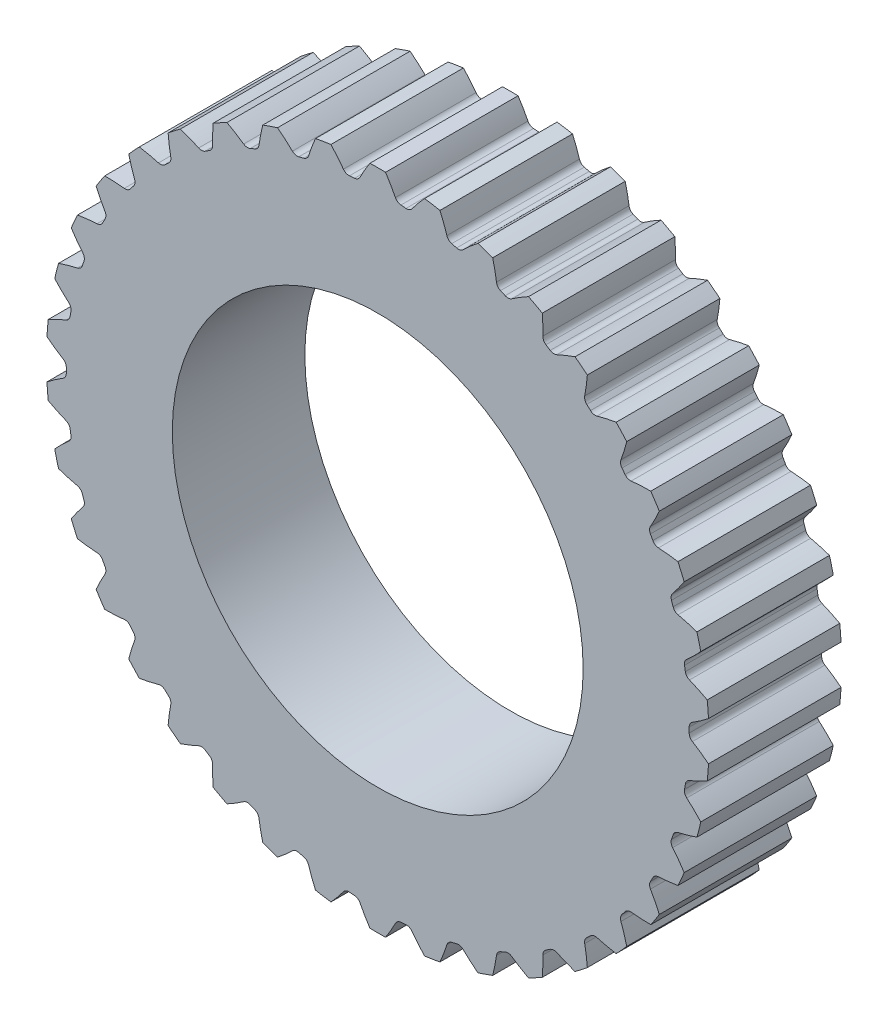
SolidWorks part; units mm, degrees
ref_plane "Спереди" through (0, 0, 0) normal (0, 0, 1) x (1, 0, 0)
ref_plane "Сверху" through (0, 0, 0) normal (0, 1, 0) x (1, 0, 0)
ref_plane "Справа" through (0, 0, 0) normal (1, 0, 0) x (0, 0, -1)
sketch "Эскиз1" plane through (0, 0, 0) normal (0, 0, 1) x (1, 0, 0)
  arc A0 (46.9984, -0.3856) -> (46.9984, 0.3856) centre (0, 0) ccw
  arc A1 (46.9984, 0.3856) -> (47.4833, 1.2601) centre (48.0145, 0.3939) cw
  arc A2 (49.9127, 2.9531) -> (49.718, 5.3026) centre (0, 0) ccw
  arc A3 (47.0431, 6.5726) -> (46.4209, 7.3554) centre (47.4245, 7.5144) cw
  arc A4 (46.4209, 7.3554) -> (46.294, 8.116) centre (0, 0) ccw
  arc A5 (46.294, 8.116) -> (46.6283, 9.0584) centre (47.2948, 8.2914) cw
  arc A6 (48.7459, 11.1281) -> (48.1672, 13.4136) centre (0, 0) ccw
  arc A7 (45.3197, 14.226) -> (44.5771, 14.8957) centre (45.5408, 15.2177) cw
  arc A8 (44.5771, 14.8957) -> (44.3267, 15.625) centre (0, 0) ccw
  arc A9 (44.3267, 15.625) -> (44.5014, 16.6096) centre (45.2851, 15.9628) cw
  arc A10 (46.2495, 18.9997) -> (45.3024, 21.1587) centre (0, 0) ccw
  arc A11 (42.36, 21.4913) -> (41.5174, 22.0297) centre (42.415, 22.506) cw
  arc A12 (41.5174, 22.0297) -> (41.1504, 22.7079) centre (0, 0) ccw
  arc A13 (41.1504, 22.7079) -> (41.1606, 23.7078) centre (42.04, 23.1988) cw
  arc A14 (42.4914, 26.353) -> (41.202, 28.3266) centre (0, 0) ccw
  arc A15 (38.2449, 28.1704) -> (37.3252, 28.5628) centre (38.1321, 29.1803) cw
  arc A16 (37.3252, 28.5628) -> (36.8515, 29.1713) centre (0, 0) ccw
  arc A17 (36.8515, 29.1713) -> (36.697, 30.1592) centre (37.6483, 29.802) cw
  arc A18 (37.5743, 32.9874) -> (35.9776, 34.7219) centre (0, 0) ccw
  arc A19 (33.0866, 34.0811) -> (32.1148, 34.3167) centre (32.8091, 35.0587) cw
  arc A20 (32.1148, 34.3167) -> (31.5475, 34.839) centre (0, 0) ccw
  arc A21 (31.5475, 34.839) -> (31.2325, 35.788) centre (32.2296, 35.5922) cw
  arc A22 (31.6323, 38.722) -> (29.7719, 40.1701) centre (0, 0) ccw
  arc A23 (27.0258, 39.0622) -> (26.0285, 39.1346) centre (26.5912, 39.9807) cw
  arc A24 (26.0285, 39.1346) -> (25.3829, 39.5564) centre (0, 0) ccw
  arc A25 (25.3829, 39.5564) -> (24.916, 40.4406) centre (25.9317, 40.4116) cw
  arc A26 (24.8275, 43.4004) -> (22.754, 44.5225) centre (0, 0) ccw
  arc A27 (20.2278, 42.9778) -> (19.2321, 42.885) centre (19.6479, 43.8122) cw
  arc A28 (19.2321, 42.885) -> (18.526, 43.1948) centre (0, 0) ccw
  arc A29 (18.526, 43.1948) -> (17.9199, 43.9901) centre (18.9265, 44.1286) cw
  arc A30 (17.3454, 46.895) -> (15.1155, 47.6605) centre (0, 0) ccw
  arc A31 (12.878, 45.721) -> (11.9112, 45.4656) centre (12.1687, 46.4486) cw
  arc A32 (11.9112, 45.4656) -> (11.1637, 45.6549) centre (0, 0) ccw
  arc A33 (11.1637, 45.6549) -> (10.4349, 46.3396) centre (11.405, 46.642) cw
  arc A34 (9.3902, 49.1103) -> (7.0647, 49.4984) centre (0, 0) ccw
  arc A35 (5.1769, 47.217) -> (4.2653, 46.8061) centre (4.3575, 47.818) cw
  arc A36 (4.2653, 46.8061) -> (3.4969, 46.8697) centre (0, 0) ccw
  arc A37 (3.4969, 46.8697) -> (2.6653, 47.4252) centre (3.5725, 47.883) cw
  arc A38 (1.1788, 49.9861) -> (-1.1788, 49.9861) centre (0, 0) ccw
  arc A39 (-2.6653, 47.4252) -> (-3.4969, 46.8697) centre (-3.5725, 47.883) cw
  arc A40 (-3.4969, 46.8697) -> (-4.2653, 46.8061) centre (0, 0) ccw
  arc A41 (-4.2653, 46.8061) -> (-5.1769, 47.217) centre (-4.3575, 47.818) cw
  arc A42 (-7.0647, 49.4984) -> (-9.3902, 49.1103) centre (0, 0) ccw
  arc A43 (-10.4349, 46.3396) -> (-11.1637, 45.6549) centre (-11.405, 46.642) cw
  arc A44 (-11.1637, 45.6549) -> (-11.9112, 45.4656) centre (0, 0) ccw
  arc A45 (-11.9112, 45.4656) -> (-12.878, 45.721) centre (-12.1687, 46.4486) cw
  arc A46 (-15.1155, 47.6605) -> (-17.3454, 46.895) centre (0, 0) ccw
  arc A47 (-17.9199, 43.9901) -> (-18.526, 43.1948) centre (-18.9265, 44.1286) cw
  arc A48 (-18.526, 43.1948) -> (-19.2321, 42.885) centre (0, 0) ccw
  arc A49 (-19.2321, 42.885) -> (-20.2278, 42.9778) centre (-19.6479, 43.8122) cw
  arc A50 (-22.754, 44.5225) -> (-24.8275, 43.4004) centre (0, 0) ccw
  arc A51 (-24.916, 40.4406) -> (-25.3829, 39.5564) centre (-25.9317, 40.4116) cw
  arc A52 (-25.3829, 39.5564) -> (-26.0285, 39.1346) centre (0, 0) ccw
  arc A53 (-26.0285, 39.1346) -> (-27.0258, 39.0622) centre (-26.5912, 39.9807) cw
  arc A54 (-29.7719, 40.1701) -> (-31.6323, 38.722) centre (0, 0) ccw
  arc A55 (-31.2325, 35.788) -> (-31.5475, 34.839) centre (-32.2296, 35.5922) cw
  arc A56 (-31.5475, 34.839) -> (-32.1148, 34.3167) centre (0, 0) ccw
  arc A57 (-32.1148, 34.3167) -> (-33.0866, 34.0811) centre (-32.8091, 35.0587) cw
  arc A58 (-35.9776, 34.7219) -> (-37.5743, 32.9874) centre (0, 0) ccw
  arc A59 (-36.697, 30.1592) -> (-36.8515, 29.1713) centre (-37.6483, 29.802) cw
  arc A60 (-36.8515, 29.1713) -> (-37.3252, 28.5628) centre (0, 0) ccw
  arc A61 (-37.3252, 28.5628) -> (-38.2449, 28.1704) centre (-38.1321, 29.1803) cw
  arc A62 (-41.202, 28.3266) -> (-42.4914, 26.353) centre (0, 0) ccw
  arc A63 (-41.1606, 23.7078) -> (-41.1504, 22.7079) centre (-42.04, 23.1988) cw
  arc A64 (-41.1504, 22.7079) -> (-41.5174, 22.0297) centre (0, 0) ccw
  arc A65 (-41.5174, 22.0297) -> (-42.36, 21.4913) centre (-42.415, 22.506) cw
  arc A66 (-45.3024, 21.1587) -> (-46.2495, 18.9997) centre (0, 0) ccw
  arc A67 (-44.5014, 16.6096) -> (-44.3267, 15.625) centre (-45.2851, 15.9628) cw
  arc A68 (-44.3267, 15.625) -> (-44.5771, 14.8957) centre (0, 0) ccw
  arc A69 (-44.5771, 14.8957) -> (-45.3197, 14.226) centre (-45.5408, 15.2177) cw
  arc A70 (-48.1672, 13.4136) -> (-48.7459, 11.1281) centre (0, 0) ccw
  arc A71 (-46.6283, 9.0584) -> (-46.294, 8.116) centre (-47.2948, 8.2914) cw
  arc A72 (-46.294, 8.116) -> (-46.4209, 7.3554) centre (0, 0) ccw
  arc A73 (-46.4209, 7.3554) -> (-47.0431, 6.5726) centre (-47.4245, 7.5144) cw
  arc A74 (-49.718, 5.3026) -> (-49.9127, 2.9531) centre (0, 0) ccw
  arc A75 (-47.4833, 1.2601) -> (-46.9984, 0.3856) centre (-48.0145, 0.3939) cw
  arc A76 (-46.9984, 0.3856) -> (-46.9984, -0.3856) centre (0, 0) ccw
  arc A77 (-46.9984, -0.3856) -> (-47.4833, -1.2601) centre (-48.0145, -0.3939) cw
  arc A78 (-49.9127, -2.9531) -> (-49.718, -5.3026) centre (0, 0) ccw
  arc A79 (-47.0431, -6.5726) -> (-46.4209, -7.3554) centre (-47.4245, -7.5144) cw
  arc A80 (-46.4209, -7.3554) -> (-46.294, -8.116) centre (0, 0) ccw
  arc A81 (-46.294, -8.116) -> (-46.6283, -9.0584) centre (-47.2948, -8.2914) cw
  arc A82 (-48.7459, -11.1281) -> (-48.1672, -13.4136) centre (0, 0) ccw
  arc A83 (-45.3197, -14.226) -> (-44.5771, -14.8957) centre (-45.5408, -15.2177) cw
  arc A84 (-44.5771, -14.8957) -> (-44.3267, -15.625) centre (0, 0) ccw
  arc A85 (-44.3267, -15.625) -> (-44.5014, -16.6096) centre (-45.2851, -15.9628) cw
  arc A86 (-46.2495, -18.9997) -> (-45.3024, -21.1587) centre (0, 0) ccw
  arc A87 (-42.36, -21.4913) -> (-41.5174, -22.0297) centre (-42.415, -22.506) cw
  arc A88 (-41.5174, -22.0297) -> (-41.1504, -22.7079) centre (0, 0) ccw
  arc A89 (-41.1504, -22.7079) -> (-41.1606, -23.7078) centre (-42.04, -23.1988) cw
  arc A90 (-42.4914, -26.353) -> (-41.202, -28.3266) centre (0, 0) ccw
  arc A91 (-38.2449, -28.1704) -> (-37.3252, -28.5628) centre (-38.1321, -29.1803) cw
  arc A92 (-37.3252, -28.5628) -> (-36.8515, -29.1713) centre (0, 0) ccw
  arc A93 (-36.8515, -29.1713) -> (-36.697, -30.1592) centre (-37.6483, -29.802) cw
  arc A94 (-37.5743, -32.9874) -> (-35.9776, -34.7219) centre (0, 0) ccw
  arc A95 (-33.0866, -34.0811) -> (-32.1148, -34.3167) centre (-32.8091, -35.0587) cw
  arc A96 (-32.1148, -34.3167) -> (-31.5475, -34.839) centre (0, 0) ccw
  arc A97 (-31.5475, -34.839) -> (-31.2325, -35.788) centre (-32.2296, -35.5922) cw
  arc A98 (-31.6323, -38.722) -> (-29.7719, -40.1701) centre (0, 0) ccw
  arc A99 (-27.0258, -39.0622) -> (-26.0285, -39.1346) centre (-26.5912, -39.9807) cw
  arc A100 (-26.0285, -39.1346) -> (-25.3829, -39.5564) centre (0, 0) ccw
  arc A101 (-25.3829, -39.5564) -> (-24.916, -40.4406) centre (-25.9317, -40.4116) cw
  arc A102 (-24.8275, -43.4004) -> (-22.754, -44.5225) centre (0, 0) ccw
  arc A103 (-20.2278, -42.9778) -> (-19.2321, -42.885) centre (-19.6479, -43.8122) cw
  arc A104 (-19.2321, -42.885) -> (-18.526, -43.1948) centre (0, 0) ccw
  arc A105 (-18.526, -43.1948) -> (-17.9199, -43.9901) centre (-18.9265, -44.1286) cw
  arc A106 (-17.3454, -46.895) -> (-15.1155, -47.6605) centre (0, 0) ccw
  arc A107 (-12.878, -45.721) -> (-11.9112, -45.4656) centre (-12.1687, -46.4486) cw
  arc A108 (-11.9112, -45.4656) -> (-11.1637, -45.6549) centre (0, 0) ccw
  arc A109 (-11.1637, -45.6549) -> (-10.4349, -46.3396) centre (-11.405, -46.642) cw
  arc A110 (-9.3902, -49.1103) -> (-7.0647, -49.4984) centre (0, 0) ccw
  arc A111 (-5.1769, -47.217) -> (-4.2653, -46.8061) centre (-4.3575, -47.818) cw
  arc A112 (-4.2653, -46.8061) -> (-3.4969, -46.8697) centre (0, 0) ccw
  arc A113 (-3.4969, -46.8697) -> (-2.6653, -47.4252) centre (-3.5725, -47.883) cw
  arc A114 (-1.1788, -49.9861) -> (1.1788, -49.9861) centre (0, 0) ccw
  arc A115 (2.6653, -47.4252) -> (3.4969, -46.8697) centre (3.5725, -47.883) cw
  arc A116 (3.4969, -46.8697) -> (4.2653, -46.8061) centre (0, 0) ccw
  arc A117 (4.2653, -46.8061) -> (5.1769, -47.217) centre (4.3575, -47.818) cw
  arc A118 (7.0647, -49.4984) -> (9.3902, -49.1103) centre (0, 0) ccw
  arc A119 (10.4349, -46.3396) -> (11.1637, -45.6549) centre (11.405, -46.642) cw
  arc A120 (11.1637, -45.6549) -> (11.9112, -45.4656) centre (0, 0) ccw
  arc A121 (11.9112, -45.4656) -> (12.878, -45.721) centre (12.1687, -46.4486) cw
  arc A122 (15.1155, -47.6605) -> (17.3454, -46.895) centre (0, 0) ccw
  arc A123 (17.9199, -43.9901) -> (18.526, -43.1948) centre (18.9265, -44.1286) cw
  arc A124 (18.526, -43.1948) -> (19.2321, -42.885) centre (0, 0) ccw
  arc A125 (19.2321, -42.885) -> (20.2278, -42.9778) centre (19.6479, -43.8122) cw
  arc A126 (22.754, -44.5225) -> (24.8275, -43.4004) centre (0, 0) ccw
  arc A127 (24.916, -40.4406) -> (25.3829, -39.5564) centre (25.9317, -40.4116) cw
  arc A128 (25.3829, -39.5564) -> (26.0285, -39.1346) centre (0, 0) ccw
  arc A129 (26.0285, -39.1346) -> (27.0258, -39.0622) centre (26.5912, -39.9807) cw
  arc A130 (29.7719, -40.1701) -> (31.6323, -38.722) centre (0, 0) ccw
  arc A131 (31.2325, -35.788) -> (31.5475, -34.839) centre (32.2296, -35.5922) cw
  arc A132 (31.5475, -34.839) -> (32.1148, -34.3167) centre (0, 0) ccw
  arc A133 (32.1148, -34.3167) -> (33.0866, -34.0811) centre (32.8091, -35.0587) cw
  arc A134 (35.9776, -34.7219) -> (37.5743, -32.9874) centre (0, 0) ccw
  arc A135 (36.697, -30.1592) -> (36.8515, -29.1713) centre (37.6483, -29.802) cw
  arc A136 (36.8515, -29.1713) -> (37.3252, -28.5628) centre (0, 0) ccw
  arc A137 (37.3252, -28.5628) -> (38.2449, -28.1704) centre (38.1321, -29.1803) cw
  arc A138 (41.202, -28.3266) -> (42.4914, -26.353) centre (0, 0) ccw
  arc A139 (41.1606, -23.7078) -> (41.1504, -22.7079) centre (42.04, -23.1988) cw
  arc A140 (41.1504, -22.7079) -> (41.5174, -22.0297) centre (0, 0) ccw
  arc A141 (41.5174, -22.0297) -> (42.36, -21.4913) centre (42.415, -22.506) cw
  arc A142 (45.3024, -21.1587) -> (46.2495, -18.9997) centre (0, 0) ccw
  arc A143 (44.5014, -16.6096) -> (44.3267, -15.625) centre (45.2851, -15.9628) cw
  arc A144 (44.3267, -15.625) -> (44.5771, -14.8957) centre (0, 0) ccw
  arc A145 (44.5771, -14.8957) -> (45.3197, -14.226) centre (45.5408, -15.2177) cw
  arc A146 (48.1672, -13.4136) -> (48.7459, -11.1281) centre (0, 0) ccw
  arc A147 (46.6283, -9.0584) -> (46.294, -8.116) centre (47.2948, -8.2914) cw
  arc A148 (46.294, -8.116) -> (46.4209, -7.3554) centre (0, 0) ccw
  arc A149 (46.4209, -7.3554) -> (47.0431, -6.5726) centre (47.4245, -7.5144) cw
  arc A150 (49.718, -5.3026) -> (49.9127, -2.9531) centre (0, 0) ccw
  arc A151 (47.4833, -1.2601) -> (46.9984, -0.3856) centre (48.0145, -0.3939) cw
  circle A152 centre (0, 0) radius 31
  spline S0 degree 3 poles (47.4833, 1.2601) (47.5346, 1.2916) (47.6115, 1.3392) (47.7138, 1.4032) (47.7905, 1.4517) (47.8672, 1.5005) (47.9438, 1.5497) (48.0203, 1.5992) (48.0968, 1.6491) (48.1732, 1.6994) (48.2496, 1.75) (48.3259, 1.801) (48.4021, 1.8523) (48.4783, 1.904) (48.5544, 1.9561) (48.6305, 2.0085) (48.7065, 2.0613) (48.7824, 2.1144) (48.8583, 2.1678) (48.934, 2.2217) (49.0098, 2.2758) (49.0854, 2.3304) (49.161, 2.3852) (49.2365, 2.4405) (49.3119, 2.496) (49.3873, 2.552) (49.4626, 2.6082) (49.5378, 2.6648) (49.613, 2.7218) (49.688, 2.7791) (49.7881, 2.856) (49.8629, 2.9141) (49.9127, 2.9531) knots 0 0 0 0 0.060998 0.091572 0.122196 0.15287 0.183594 0.214368 0.245192 0.276067 0.306991 0.337966 0.36899 0.400065 0.43119 0.462365 0.49359 0.524865 0.55619 0.587565 0.61899 0.650466 0.681991 0.713567 0.745192 0.776868 0.808594 0.84037 0.872196 0.904072 0.935998 1 1 1 1
  spline S1 degree 3 poles (49.718, 5.3026) (49.6625, 5.3328) (49.5791, 5.3778) (49.4678, 5.4372) (49.3843, 5.4814) (49.3008, 5.5252) (49.2173, 5.5686) (49.1338, 5.6117) (49.0502, 5.6545) (48.9667, 5.6969) (48.8831, 5.7389) (48.7995, 5.7806) (48.7159, 5.8219) (48.6323, 5.8629) (48.5487, 5.9035) (48.4651, 5.9438) (48.3815, 5.9837) (48.2978, 6.0232) (48.2142, 6.0624) (48.1305, 6.1012) (48.0469, 6.1397) (47.9632, 6.1778) (47.8796, 6.2155) (47.7959, 6.2529) (47.7123, 6.2899) (47.6286, 6.3265) (47.545, 6.3628) (47.4613, 6.3987) (47.3777, 6.4342) (47.294, 6.4694) (47.1826, 6.5157) (47.0989, 6.55) (47.0431, 6.5726) knots 0 0 0 0 0.064002 0.095928 0.127804 0.15963 0.191406 0.223132 0.254808 0.286433 0.318009 0.349534 0.38101 0.412435 0.44381 0.475135 0.50641 0.537635 0.56881 0.599935 0.63101 0.662034 0.693009 0.723933 0.754808 0.785632 0.816406 0.84713 0.877804 0.908428 0.939002 1 1 1 1
  spline S2 degree 3 poles (46.6283, 9.0584) (46.6737, 9.0979) (46.7418, 9.1575) (46.8321, 9.2375) (46.8998, 9.2979) (46.9674, 9.3587) (47.0348, 9.4198) (47.1022, 9.4813) (47.1694, 9.5431) (47.2365, 9.6052) (47.3035, 9.6677) (47.3704, 9.7306) (47.4371, 9.7938) (47.5037, 9.8573) (47.5703, 9.9212) (47.6366, 9.9854) (47.7029, 10.05) (47.7691, 10.1149) (47.8351, 10.1801) (47.901, 10.2456) (47.9667, 10.3115) (48.0324, 10.3778) (48.0979, 10.4443) (48.1633, 10.5112) (48.2286, 10.5785) (48.2937, 10.646) (48.3587, 10.7139) (48.4236, 10.7821) (48.4883, 10.8507) (48.5529, 10.9196) (48.639, 11.0119) (48.7032, 11.0815) (48.7459, 11.1281) knots 0 0 0 0 0.060998 0.091572 0.122196 0.15287 0.183594 0.214368 0.245192 0.276067 0.306991 0.337966 0.36899 0.400065 0.43119 0.462365 0.49359 0.524865 0.55619 0.587565 0.61899 0.650466 0.681991 0.713567 0.745192 0.776868 0.808594 0.84037 0.872196 0.904072 0.935998 1 1 1 1
  spline S3 degree 3 poles (48.1672, 13.4136) (48.1074, 13.4342) (48.0178, 13.4649) (47.8982, 13.5052) (47.8086, 13.535) (47.719, 13.5645) (47.6295, 13.5936) (47.54, 13.6223) (47.4505, 13.6508) (47.3612, 13.6788) (47.2718, 13.7065) (47.1825, 13.7339) (47.0932, 13.7609) (47.004, 13.7876) (46.9149, 13.8139) (46.8258, 13.8398) (46.7367, 13.8654) (46.6477, 13.8906) (46.5588, 13.9155) (46.4699, 13.94) (46.381, 13.9642) (46.2922, 13.988) (46.2035, 14.0114) (46.1149, 14.0345) (46.0263, 14.0573) (45.9377, 14.0796) (45.8492, 14.1016) (45.7608, 14.1233) (45.6725, 14.1445) (45.5842, 14.1655) (45.4666, 14.1928) (45.3785, 14.2129) (45.3197, 14.226) knots 0 0 0 0 0.064002 0.095928 0.127804 0.15963 0.191406 0.223132 0.254808 0.286433 0.318009 0.349534 0.38101 0.412435 0.44381 0.475135 0.50641 0.537635 0.56881 0.599935 0.63101 0.662034 0.693009 0.723933 0.754808 0.785632 0.816406 0.84713 0.877804 0.908428 0.939002 1 1 1 1
  spline S4 degree 3 poles (44.5014, 16.6096) (44.5397, 16.6561) (44.597, 16.726) (44.6729, 16.8198) (44.7298, 16.8906) (44.7864, 16.9616) (44.8429, 17.033) (44.8992, 17.1047) (44.9553, 17.1768) (45.0113, 17.2491) (45.0671, 17.3218) (45.1227, 17.3948) (45.1781, 17.4681) (45.2334, 17.5417) (45.2885, 17.6157) (45.3434, 17.69) (45.3981, 17.7645) (45.4527, 17.8394) (45.5071, 17.9146) (45.5613, 17.9902) (45.6153, 18.066) (45.6692, 18.1421) (45.7228, 18.2186) (45.7763, 18.2953) (45.8296, 18.3724) (45.8827, 18.4497) (45.9357, 18.5274) (45.9885, 18.6054) (46.041, 18.6836) (46.0934, 18.7622) (46.1631, 18.8674) (46.215, 18.9467) (46.2495, 18.9997) knots 0 0 0 0 0.060998 0.091572 0.122196 0.15287 0.183594 0.214368 0.245192 0.276067 0.306991 0.337966 0.36899 0.400065 0.43119 0.462365 0.49359 0.524865 0.55619 0.587565 0.61899 0.650466 0.681991 0.713567 0.745192 0.776868 0.808594 0.84037 0.872196 0.904072 0.935998 1 1 1 1
  spline S5 degree 3 poles (45.3024, 21.1587) (45.2401, 21.1692) (45.1466, 21.1847) (45.022, 21.2048) (44.9287, 21.2194) (44.8355, 21.2337) (44.7424, 21.2477) (44.6494, 21.2614) (44.5565, 21.2747) (44.4637, 21.2877) (44.3711, 21.3003) (44.2785, 21.3126) (44.186, 21.3245) (44.0936, 21.3361) (44.0013, 21.3474) (43.9092, 21.3583) (43.8171, 21.3689) (43.7252, 21.3791) (43.6333, 21.389) (43.5416, 21.3986) (43.45, 21.4078) (43.3585, 21.4167) (43.2672, 21.4252) (43.1759, 21.4334) (43.0848, 21.4412) (42.9938, 21.4487) (42.9029, 21.4558) (42.8121, 21.4626) (42.7214, 21.4691) (42.6309, 21.4752) (42.5105, 21.4828) (42.4202, 21.4881) (42.36, 21.4913) knots 0 0 0 0 0.064002 0.095928 0.127804 0.15963 0.191406 0.223132 0.254808 0.286433 0.318009 0.349534 0.38101 0.412435 0.44381 0.475135 0.50641 0.537635 0.56881 0.599935 0.63101 0.662034 0.693009 0.723933 0.754808 0.785632 0.816406 0.84713 0.877804 0.908428 0.939002 1 1 1 1
  spline S6 degree 3 poles (41.1606, 23.7078) (41.1907, 23.7599) (41.2357, 23.8383) (41.2952, 23.9434) (41.3396, 24.0225) (41.3838, 24.1019) (41.4277, 24.1816) (41.4715, 24.2616) (41.515, 24.3419) (41.5583, 24.4225) (41.6013, 24.5033) (41.6442, 24.5845) (41.6868, 24.6659) (41.7292, 24.7477) (41.7714, 24.8297) (41.8133, 24.912) (41.855, 24.9945) (41.8965, 25.0774) (41.9378, 25.1605) (41.9788, 25.2439) (42.0196, 25.3276) (42.0602, 25.4116) (42.1005, 25.4958) (42.1407, 25.5803) (42.1806, 25.6651) (42.2202, 25.7501) (42.2597, 25.8355) (42.2989, 25.9211) (42.3379, 26.0069) (42.3766, 26.093) (42.428, 26.2083) (42.4662, 26.295) (42.4914, 26.353) knots 0 0 0 0 0.060998 0.091572 0.122196 0.15287 0.183594 0.214368 0.245192 0.276067 0.306991 0.337966 0.36899 0.400065 0.43119 0.462365 0.49359 0.524865 0.55619 0.587565 0.61899 0.650466 0.681991 0.713567 0.745192 0.776868 0.808594 0.84037 0.872196 0.904072 0.935998 1 1 1 1
  spline S7 degree 3 poles (41.202, 28.3266) (41.1387, 28.3268) (41.044, 28.3267) (40.9178, 28.3259) (40.8234, 28.325) (40.7291, 28.3238) (40.6349, 28.3223) (40.541, 28.3205) (40.4471, 28.3183) (40.3535, 28.3158) (40.26, 28.313) (40.1666, 28.3099) (40.0734, 28.3065) (39.9804, 28.3027) (39.8875, 28.2986) (39.7948, 28.2942) (39.7023, 28.2895) (39.6099, 28.2845) (39.5177, 28.2791) (39.4257, 28.2735) (39.3338, 28.2675) (39.2421, 28.2612) (39.1506, 28.2545) (39.0592, 28.2476) (38.968, 28.2403) (38.877, 28.2327) (38.7862, 28.2248) (38.6955, 28.2165) (38.6051, 28.208) (38.5148, 28.1991) (38.3947, 28.1868) (38.3048, 28.1771) (38.2449, 28.1704) knots 0 0 0 0 0.064002 0.095928 0.127804 0.15963 0.191406 0.223132 0.254808 0.286433 0.318009 0.349534 0.38101 0.412435 0.44381 0.475135 0.50641 0.537635 0.56881 0.599935 0.63101 0.662034 0.693009 0.723933 0.754808 0.785632 0.816406 0.84713 0.877804 0.908428 0.939002 1 1 1 1
  spline S8 degree 3 poles (36.697, 30.1592) (36.7182, 30.2156) (36.7497, 30.3004) (36.791, 30.4138) (36.8218, 30.4991) (36.8523, 30.5847) (36.8826, 30.6706) (36.9125, 30.7567) (36.9422, 30.843) (36.9717, 30.9297) (37.0008, 31.0165) (37.0297, 31.1036) (37.0584, 31.191) (37.0867, 31.2785) (37.1148, 31.3664) (37.1426, 31.4544) (37.1702, 31.5428) (37.1975, 31.6313) (37.2245, 31.7201) (37.2513, 31.8091) (37.2777, 31.8984) (37.3039, 31.9879) (37.3299, 32.0776) (37.3555, 32.1676) (37.3809, 32.2577) (37.4061, 32.3482) (37.4309, 32.4388) (37.4555, 32.5297) (37.4798, 32.6208) (37.5039, 32.7121) (37.5356, 32.8343) (37.559, 32.9261) (37.5743, 32.9874) knots 0 0 0 0 0.060998 0.091572 0.122196 0.15287 0.183594 0.214368 0.245192 0.276067 0.306991 0.337966 0.36899 0.400065 0.43119 0.462365 0.49359 0.524865 0.55619 0.587565 0.61899 0.650466 0.681991 0.713567 0.745192 0.776868 0.808594 0.84037 0.872196 0.904072 0.935998 1 1 1 1
  spline S9 degree 3 poles (35.9776, 34.7219) (35.9152, 34.7117) (35.8218, 34.696) (35.6974, 34.6744) (35.6044, 34.658) (35.5116, 34.6413) (35.419, 34.6243) (35.3267, 34.607) (35.2345, 34.5895) (35.1425, 34.5716) (35.0507, 34.5534) (34.9592, 34.535) (34.8678, 34.5163) (34.7767, 34.4972) (34.6857, 34.4779) (34.595, 34.4583) (34.5045, 34.4385) (34.4142, 34.4183) (34.3242, 34.3978) (34.2343, 34.3771) (34.1447, 34.3561) (34.0553, 34.3347) (33.9661, 34.3131) (33.8771, 34.2912) (33.7884, 34.2691) (33.6999, 34.2466) (33.6116, 34.2238) (33.5235, 34.2008) (33.4357, 34.1774) (33.3481, 34.1538) (33.2317, 34.122) (33.1446, 34.0976) (33.0866, 34.0811) knots 0 0 0 0 0.064002 0.095928 0.127804 0.15963 0.191406 0.223132 0.254808 0.286433 0.318009 0.349534 0.38101 0.412435 0.44381 0.475135 0.50641 0.537635 0.56881 0.599935 0.63101 0.662034 0.693009 0.723933 0.754808 0.785632 0.816406 0.84713 0.877804 0.908428 0.939002 1 1 1 1
  spline S10 degree 3 poles (31.2325, 35.788) (31.2441, 35.8471) (31.2612, 35.9359) (31.2833, 36.0546) (31.2996, 36.1438) (31.3156, 36.2333) (31.3313, 36.3229) (31.3467, 36.4128) (31.3618, 36.5029) (31.3766, 36.5932) (31.391, 36.6836) (31.4052, 36.7743) (31.4191, 36.8652) (31.4326, 36.9562) (31.4459, 37.0475) (31.4588, 37.1389) (31.4715, 37.2306) (31.4838, 37.3224) (31.4959, 37.4144) (31.5076, 37.5066) (31.519, 37.599) (31.5301, 37.6916) (31.5409, 37.7844) (31.5515, 37.8774) (31.5617, 37.9705) (31.5716, 38.0638) (31.5812, 38.1573) (31.5905, 38.251) (31.5995, 38.3449) (31.6081, 38.4389) (31.6193, 38.5646) (31.6273, 38.659) (31.6323, 38.722) knots 0 0 0 0 0.060998 0.091572 0.122196 0.15287 0.183594 0.214368 0.245192 0.276067 0.306991 0.337966 0.36899 0.400065 0.43119 0.462365 0.49359 0.524865 0.55619 0.587565 0.61899 0.650466 0.681991 0.713567 0.745192 0.776868 0.808594 0.84037 0.872196 0.904072 0.935998 1 1 1 1
  spline S11 degree 3 poles (29.7719, 40.1701) (29.712, 40.1497) (29.6225, 40.1188) (29.5033, 40.0771) (29.4143, 40.0456) (29.3255, 40.0139) (29.237, 39.9819) (29.1487, 39.9496) (29.0607, 39.9171) (28.9729, 39.8843) (28.8854, 39.8513) (28.7981, 39.8181) (28.7111, 39.7846) (28.6243, 39.7508) (28.5378, 39.7168) (28.4515, 39.6825) (28.3655, 39.648) (28.2798, 39.6133) (28.1943, 39.5783) (28.1091, 39.543) (28.0242, 39.5075) (27.9395, 39.4718) (27.8551, 39.4358) (27.7709, 39.3995) (27.687, 39.3631) (27.6034, 39.3263) (27.5201, 39.2893) (27.437, 39.2521) (27.3542, 39.2146) (27.2717, 39.1769) (27.1621, 39.1263) (27.0803, 39.088) (27.0258, 39.0622) knots 0 0 0 0 0.064002 0.095928 0.127804 0.15963 0.191406 0.223132 0.254808 0.286433 0.318009 0.349534 0.38101 0.412435 0.44381 0.475135 0.50641 0.537635 0.56881 0.599935 0.63101 0.662034 0.693009 0.723933 0.754808 0.785632 0.816406 0.84713 0.877804 0.908428 0.939002 1 1 1 1
  spline S12 degree 3 poles (24.916, 40.4406) (24.9177, 40.5008) (24.9199, 40.5912) (24.9223, 40.7119) (24.9237, 40.8026) (24.9247, 40.8935) (24.9254, 40.9845) (24.9258, 41.0757) (24.9259, 41.167) (24.9256, 41.2585) (24.925, 41.3501) (24.924, 41.4419) (24.9228, 41.5338) (24.9211, 41.6258) (24.9192, 41.718) (24.9169, 41.8104) (24.9143, 41.9028) (24.9114, 41.9954) (24.9081, 42.0882) (24.9045, 42.1811) (24.9005, 42.2741) (24.8963, 42.3673) (24.8917, 42.4605) (24.8867, 42.554) (24.8815, 42.6475) (24.8759, 42.7412) (24.87, 42.835) (24.8637, 42.9289) (24.8571, 43.023) (24.8502, 43.1172) (24.8406, 43.243) (24.8328, 43.3374) (24.8275, 43.4004) knots 0 0 0 0 0.060998 0.091572 0.122196 0.15287 0.183594 0.214368 0.245192 0.276067 0.306991 0.337966 0.36899 0.400065 0.43119 0.462365 0.49359 0.524865 0.55619 0.587565 0.61899 0.650466 0.681991 0.713567 0.745192 0.776868 0.808594 0.84037 0.872196 0.904072 0.935998 1 1 1 1
  spline S13 degree 3 poles (22.754, 44.5225) (22.6984, 44.4926) (22.6151, 44.4474) (22.5045, 44.3866) (22.4218, 44.3409) (22.3395, 44.295) (22.2574, 44.2488) (22.1757, 44.2025) (22.0942, 44.1559) (22.013, 44.1091) (21.9321, 44.0622) (21.8515, 44.015) (21.7712, 43.9676) (21.6911, 43.9201) (21.6114, 43.8723) (21.532, 43.8243) (21.4528, 43.7761) (21.374, 43.7277) (21.2954, 43.6791) (21.2172, 43.6303) (21.1392, 43.5813) (21.0616, 43.5321) (20.9842, 43.4827) (20.9072, 43.4331) (20.8305, 43.3833) (20.7541, 43.3333) (20.6779, 43.2831) (20.6021, 43.2328) (20.5266, 43.1822) (20.4515, 43.1314) (20.3517, 43.0634) (20.2772, 43.0121) (20.2278, 42.9778) knots 0 0 0 0 0.064002 0.095928 0.127804 0.15963 0.191406 0.223132 0.254808 0.286433 0.318009 0.349534 0.38101 0.412435 0.44381 0.475135 0.50641 0.537635 0.56881 0.599935 0.63101 0.662034 0.693009 0.723933 0.754808 0.785632 0.816406 0.84713 0.877804 0.908428 0.939002 1 1 1 1
  spline S14 degree 3 poles (17.9199, 43.9901) (17.9116, 44.0498) (17.899, 44.1393) (17.8814, 44.2587) (17.8678, 44.3484) (17.8539, 44.4382) (17.8397, 44.5281) (17.825, 44.6181) (17.8101, 44.7082) (17.7947, 44.7984) (17.779, 44.8887) (17.763, 44.979) (17.7466, 45.0695) (17.7299, 45.16) (17.7128, 45.2506) (17.6953, 45.3413) (17.6775, 45.4321) (17.6594, 45.523) (17.6409, 45.6139) (17.622, 45.7049) (17.6028, 45.796) (17.5833, 45.8872) (17.5634, 45.9785) (17.5432, 46.0698) (17.5226, 46.1612) (17.5016, 46.2527) (17.4804, 46.3442) (17.4587, 46.4359) (17.4368, 46.5276) (17.4144, 46.6193) (17.3842, 46.7419) (17.361, 46.8337) (17.3454, 46.895) knots 0 0 0 0 0.060998 0.091572 0.122196 0.15287 0.183594 0.214368 0.245192 0.276067 0.306991 0.337966 0.36899 0.400065 0.43119 0.462365 0.49359 0.524865 0.55619 0.587565 0.61899 0.650466 0.681991 0.713567 0.745192 0.776868 0.808594 0.84037 0.872196 0.904072 0.935998 1 1 1 1
  spline S15 degree 3 poles (15.1155, 47.6605) (15.0656, 47.6218) (14.9909, 47.5635) (14.8917, 47.4854) (14.8178, 47.4267) (14.7441, 47.3678) (14.6708, 47.3088) (14.5977, 47.2496) (14.525, 47.1903) (14.4526, 47.1308) (14.3806, 47.0711) (14.3088, 47.0113) (14.2374, 46.9514) (14.1663, 46.8913) (14.0955, 46.831) (14.025, 46.7706) (13.9549, 46.7101) (13.8851, 46.6494) (13.8156, 46.5885) (13.7465, 46.5275) (13.6777, 46.4663) (13.6092, 46.405) (13.541, 46.3436) (13.4732, 46.282) (13.4057, 46.2202) (13.3386, 46.1583) (13.2717, 46.0963) (13.2053, 46.0341) (13.1391, 45.9718) (13.0733, 45.9093) (12.9861, 45.8259) (12.9211, 45.763) (12.878, 45.721) knots 0 0 0 0 0.064002 0.095928 0.127804 0.15963 0.191406 0.223132 0.254808 0.286433 0.318009 0.349534 0.38101 0.412435 0.44381 0.475135 0.50641 0.537635 0.56881 0.599935 0.63101 0.662034 0.693009 0.723933 0.754808 0.785632 0.816406 0.84713 0.877804 0.908428 0.939002 1 1 1 1
  spline S16 degree 3 poles (10.4349, 46.3396) (10.417, 46.3972) (10.3898, 46.4834) (10.3528, 46.5983) (10.3246, 46.6845) (10.2961, 46.7708) (10.2673, 46.8571) (10.238, 46.9435) (10.2084, 47.0299) (10.1785, 47.1163) (10.1481, 47.2028) (10.1174, 47.2893) (10.0864, 47.3758) (10.055, 47.4623) (10.0232, 47.5489) (9.991, 47.6355) (9.9586, 47.7221) (9.9257, 47.8087) (9.8925, 47.8954) (9.8589, 47.9821) (9.825, 48.0688) (9.7907, 48.1555) (9.7561, 48.2422) (9.7211, 48.329) (9.6857, 48.4157) (9.65, 48.5025) (9.6139, 48.5893) (9.5775, 48.6762) (9.5408, 48.763) (9.5036, 48.8498) (9.4536, 48.9657) (9.4157, 49.0525) (9.3902, 49.1103) knots 0 0 0 0 0.060998 0.091572 0.122196 0.15287 0.183594 0.214368 0.245192 0.276067 0.306991 0.337966 0.36899 0.400065 0.43119 0.462365 0.49359 0.524865 0.55619 0.587565 0.61899 0.650466 0.681991 0.713567 0.745192 0.776868 0.808594 0.84037 0.872196 0.904072 0.935998 1 1 1 1
  spline S17 degree 3 poles (7.0647, 49.4984) (7.0218, 49.452) (6.9577, 49.3822) (6.8728, 49.2888) (6.8095, 49.2188) (6.7465, 49.1486) (6.6839, 49.0783) (6.6216, 49.0079) (6.5597, 48.9374) (6.4981, 48.8668) (6.4368, 48.7961) (6.3759, 48.7253) (6.3153, 48.6544) (6.255, 48.5834) (6.1951, 48.5124) (6.1356, 48.4412) (6.0764, 48.3699) (6.0175, 48.2985) (5.959, 48.2271) (5.9008, 48.1555) (5.843, 48.0839) (5.7855, 48.0121) (5.7284, 47.9403) (5.6717, 47.8684) (5.6153, 47.7964) (5.5592, 47.7243) (5.5035, 47.6521) (5.4482, 47.5798) (5.3932, 47.5074) (5.3386, 47.435) (5.2663, 47.3383) (5.2126, 47.2656) (5.1769, 47.217) knots 0 0 0 0 0.064002 0.095928 0.127804 0.15963 0.191406 0.223132 0.254808 0.286433 0.318009 0.349534 0.38101 0.412435 0.44381 0.475135 0.50641 0.537635 0.56881 0.599935 0.63101 0.662034 0.693009 0.723933 0.754808 0.785632 0.816406 0.84713 0.877804 0.908428 0.939002 1 1 1 1
  spline S18 degree 3 poles (2.6653, 47.4252) (2.6382, 47.4789) (2.5971, 47.5595) (2.5418, 47.6667) (2.4998, 47.7472) (2.4575, 47.8276) (2.4148, 47.908) (2.3717, 47.9884) (2.3283, 48.0687) (2.2845, 48.149) (2.2404, 48.2293) (2.1959, 48.3096) (2.151, 48.3898) (2.1058, 48.47) (2.0602, 48.5501) (2.0142, 48.6302) (1.9679, 48.7103) (1.9213, 48.7904) (1.8742, 48.8704) (1.8269, 48.9504) (1.7791, 49.0303) (1.731, 49.1102) (1.6826, 49.1901) (1.6338, 49.2699) (1.5846, 49.3496) (1.5351, 49.4294) (1.4853, 49.509) (1.4351, 49.5887) (1.3845, 49.6683) (1.3336, 49.7478) (1.2652, 49.8539) (1.2135, 49.9333) (1.1788, 49.9861) knots 0 0 0 0 0.060998 0.091572 0.122196 0.15287 0.183594 0.214368 0.245192 0.276067 0.306991 0.337966 0.36899 0.400065 0.43119 0.462365 0.49359 0.524865 0.55619 0.587565 0.61899 0.650466 0.681991 0.713567 0.745192 0.776868 0.808594 0.84037 0.872196 0.904072 0.935998 1 1 1 1
  spline S19 degree 3 poles (-1.1788, 49.9861) (-1.2135, 49.9333) (-1.2652, 49.8539) (-1.3336, 49.7478) (-1.3845, 49.6683) (-1.4351, 49.5887) (-1.4853, 49.509) (-1.5351, 49.4294) (-1.5846, 49.3496) (-1.6338, 49.2699) (-1.6826, 49.1901) (-1.731, 49.1102) (-1.7791, 49.0303) (-1.8269, 48.9504) (-1.8742, 48.8704) (-1.9213, 48.7904) (-1.9679, 48.7103) (-2.0142, 48.6302) (-2.0602, 48.5501) (-2.1058, 48.47) (-2.151, 48.3898) (-2.1959, 48.3096) (-2.2404, 48.2293) (-2.2845, 48.149) (-2.3283, 48.0687) (-2.3717, 47.9884) (-2.4148, 47.908) (-2.4575, 47.8276) (-2.4998, 47.7472) (-2.5418, 47.6667) (-2.5971, 47.5595) (-2.6382, 47.4789) (-2.6653, 47.4252) knots 0 0 0 0 0.064002 0.095928 0.127804 0.15963 0.191406 0.223132 0.254808 0.286433 0.318009 0.349534 0.38101 0.412435 0.44381 0.475135 0.50641 0.537635 0.56881 0.599935 0.63101 0.662034 0.693009 0.723933 0.754808 0.785632 0.816406 0.84713 0.877804 0.908428 0.939002 1 1 1 1
  spline S20 degree 3 poles (-5.1769, 47.217) (-5.2126, 47.2656) (-5.2663, 47.3383) (-5.3386, 47.435) (-5.3932, 47.5074) (-5.4482, 47.5798) (-5.5035, 47.6521) (-5.5592, 47.7243) (-5.6153, 47.7964) (-5.6717, 47.8684) (-5.7284, 47.9403) (-5.7855, 48.0121) (-5.843, 48.0839) (-5.9008, 48.1555) (-5.959, 48.2271) (-6.0175, 48.2985) (-6.0764, 48.3699) (-6.1356, 48.4412) (-6.1951, 48.5124) (-6.255, 48.5834) (-6.3153, 48.6544) (-6.3759, 48.7253) (-6.4368, 48.7961) (-6.4981, 48.8668) (-6.5597, 48.9374) (-6.6216, 49.0079) (-6.6839, 49.0783) (-6.7465, 49.1486) (-6.8095, 49.2188) (-6.8728, 49.2888) (-6.9577, 49.3822) (-7.0218, 49.452) (-7.0647, 49.4984) knots 0 0 0 0 0.060998 0.091572 0.122196 0.15287 0.183594 0.214368 0.245192 0.276067 0.306991 0.337966 0.36899 0.400065 0.43119 0.462365 0.49359 0.524865 0.55619 0.587565 0.61899 0.650466 0.681991 0.713567 0.745192 0.776868 0.808594 0.84037 0.872196 0.904072 0.935998 1 1 1 1
  spline S21 degree 3 poles (-9.3902, 49.1103) (-9.4157, 49.0525) (-9.4536, 48.9657) (-9.5036, 48.8498) (-9.5408, 48.763) (-9.5775, 48.6762) (-9.6139, 48.5893) (-9.65, 48.5025) (-9.6857, 48.4157) (-9.7211, 48.329) (-9.7561, 48.2422) (-9.7907, 48.1555) (-9.825, 48.0688) (-9.8589, 47.9821) (-9.8925, 47.8954) (-9.9257, 47.8087) (-9.9586, 47.7221) (-9.991, 47.6355) (-10.0232, 47.5489) (-10.055, 47.4623) (-10.0864, 47.3758) (-10.1174, 47.2893) (-10.1481, 47.2028) (-10.1785, 47.1163) (-10.2084, 47.0299) (-10.238, 46.9435) (-10.2673, 46.8571) (-10.2961, 46.7708) (-10.3246, 46.6845) (-10.3528, 46.5983) (-10.3898, 46.4834) (-10.417, 46.3972) (-10.4349, 46.3396) knots 0 0 0 0 0.064002 0.095928 0.127804 0.15963 0.191406 0.223132 0.254808 0.286433 0.318009 0.349534 0.38101 0.412435 0.44381 0.475135 0.50641 0.537635 0.56881 0.599935 0.63101 0.662034 0.693009 0.723933 0.754808 0.785632 0.816406 0.84713 0.877804 0.908428 0.939002 1 1 1 1
  spline S22 degree 3 poles (-12.878, 45.721) (-12.9211, 45.763) (-12.9861, 45.8259) (-13.0733, 45.9093) (-13.1391, 45.9718) (-13.2053, 46.0341) (-13.2717, 46.0963) (-13.3386, 46.1583) (-13.4057, 46.2202) (-13.4732, 46.282) (-13.541, 46.3436) (-13.6092, 46.405) (-13.6777, 46.4663) (-13.7465, 46.5275) (-13.8156, 46.5885) (-13.8851, 46.6494) (-13.9549, 46.7101) (-14.025, 46.7706) (-14.0955, 46.831) (-14.1663, 46.8913) (-14.2374, 46.9514) (-14.3088, 47.0113) (-14.3806, 47.0711) (-14.4526, 47.1308) (-14.525, 47.1903) (-14.5977, 47.2496) (-14.6708, 47.3088) (-14.7441, 47.3678) (-14.8178, 47.4267) (-14.8917, 47.4854) (-14.9909, 47.5635) (-15.0656, 47.6218) (-15.1155, 47.6605) knots 0 0 0 0 0.060998 0.091572 0.122196 0.15287 0.183594 0.214368 0.245192 0.276067 0.306991 0.337966 0.36899 0.400065 0.43119 0.462365 0.49359 0.524865 0.55619 0.587565 0.61899 0.650466 0.681991 0.713567 0.745192 0.776868 0.808594 0.84037 0.872196 0.904072 0.935998 1 1 1 1
  spline S23 degree 3 poles (-17.3454, 46.895) (-17.361, 46.8337) (-17.3842, 46.7419) (-17.4144, 46.6193) (-17.4368, 46.5276) (-17.4587, 46.4359) (-17.4804, 46.3442) (-17.5016, 46.2527) (-17.5226, 46.1612) (-17.5432, 46.0698) (-17.5634, 45.9785) (-17.5833, 45.8872) (-17.6028, 45.796) (-17.622, 45.7049) (-17.6409, 45.6139) (-17.6594, 45.523) (-17.6775, 45.4321) (-17.6953, 45.3413) (-17.7128, 45.2506) (-17.7299, 45.16) (-17.7466, 45.0695) (-17.763, 44.979) (-17.779, 44.8887) (-17.7947, 44.7984) (-17.8101, 44.7082) (-17.825, 44.6181) (-17.8397, 44.5281) (-17.8539, 44.4382) (-17.8678, 44.3484) (-17.8814, 44.2587) (-17.899, 44.1393) (-17.9116, 44.0498) (-17.9199, 43.9901) knots 0 0 0 0 0.064002 0.095928 0.127804 0.15963 0.191406 0.223132 0.254808 0.286433 0.318009 0.349534 0.38101 0.412435 0.44381 0.475135 0.50641 0.537635 0.56881 0.599935 0.63101 0.662034 0.693009 0.723933 0.754808 0.785632 0.816406 0.84713 0.877804 0.908428 0.939002 1 1 1 1
  spline S24 degree 3 poles (-20.2278, 42.9778) (-20.2772, 43.0121) (-20.3517, 43.0634) (-20.4515, 43.1314) (-20.5266, 43.1822) (-20.6021, 43.2328) (-20.6779, 43.2831) (-20.7541, 43.3333) (-20.8305, 43.3833) (-20.9072, 43.4331) (-20.9842, 43.4827) (-21.0616, 43.5321) (-21.1392, 43.5813) (-21.2172, 43.6303) (-21.2954, 43.6791) (-21.374, 43.7277) (-21.4528, 43.7761) (-21.532, 43.8243) (-21.6114, 43.8723) (-21.6911, 43.9201) (-21.7712, 43.9676) (-21.8515, 44.015) (-21.9321, 44.0622) (-22.013, 44.1091) (-22.0942, 44.1559) (-22.1757, 44.2025) (-22.2574, 44.2488) (-22.3395, 44.295) (-22.4218, 44.3409) (-22.5045, 44.3866) (-22.6151, 44.4474) (-22.6984, 44.4926) (-22.754, 44.5225) knots 0 0 0 0 0.060998 0.091572 0.122196 0.15287 0.183594 0.214368 0.245192 0.276067 0.306991 0.337966 0.36899 0.400065 0.43119 0.462365 0.49359 0.524865 0.55619 0.587565 0.61899 0.650466 0.681991 0.713567 0.745192 0.776868 0.808594 0.84037 0.872196 0.904072 0.935998 1 1 1 1
  spline S25 degree 3 poles (-24.8275, 43.4004) (-24.8328, 43.3374) (-24.8406, 43.243) (-24.8502, 43.1172) (-24.8571, 43.023) (-24.8637, 42.9289) (-24.87, 42.835) (-24.8759, 42.7412) (-24.8815, 42.6475) (-24.8867, 42.554) (-24.8917, 42.4605) (-24.8963, 42.3673) (-24.9005, 42.2741) (-24.9045, 42.1811) (-24.9081, 42.0882) (-24.9114, 41.9954) (-24.9143, 41.9028) (-24.9169, 41.8104) (-24.9192, 41.718) (-24.9211, 41.6258) (-24.9228, 41.5338) (-24.924, 41.4419) (-24.925, 41.3501) (-24.9256, 41.2585) (-24.9259, 41.167) (-24.9258, 41.0757) (-24.9254, 40.9845) (-24.9247, 40.8935) (-24.9237, 40.8026) (-24.9223, 40.7119) (-24.9199, 40.5912) (-24.9177, 40.5008) (-24.916, 40.4406) knots 0 0 0 0 0.064002 0.095928 0.127804 0.15963 0.191406 0.223132 0.254808 0.286433 0.318009 0.349534 0.38101 0.412435 0.44381 0.475135 0.50641 0.537635 0.56881 0.599935 0.63101 0.662034 0.693009 0.723933 0.754808 0.785632 0.816406 0.84713 0.877804 0.908428 0.939002 1 1 1 1
  spline S26 degree 3 poles (-27.0258, 39.0622) (-27.0803, 39.088) (-27.1621, 39.1263) (-27.2717, 39.1769) (-27.3542, 39.2146) (-27.437, 39.2521) (-27.5201, 39.2893) (-27.6034, 39.3263) (-27.687, 39.3631) (-27.7709, 39.3995) (-27.8551, 39.4358) (-27.9395, 39.4718) (-28.0242, 39.5075) (-28.1091, 39.543) (-28.1943, 39.5783) (-28.2798, 39.6133) (-28.3655, 39.648) (-28.4515, 39.6825) (-28.5378, 39.7168) (-28.6243, 39.7508) (-28.7111, 39.7846) (-28.7981, 39.8181) (-28.8854, 39.8513) (-28.9729, 39.8843) (-29.0607, 39.9171) (-29.1487, 39.9496) (-29.237, 39.9819) (-29.3255, 40.0139) (-29.4143, 40.0456) (-29.5033, 40.0771) (-29.6225, 40.1188) (-29.712, 40.1497) (-29.7719, 40.1701) knots 0 0 0 0 0.060998 0.091572 0.122196 0.15287 0.183594 0.214368 0.245192 0.276067 0.306991 0.337966 0.36899 0.400065 0.43119 0.462365 0.49359 0.524865 0.55619 0.587565 0.61899 0.650466 0.681991 0.713567 0.745192 0.776868 0.808594 0.84037 0.872196 0.904072 0.935998 1 1 1 1
  spline S27 degree 3 poles (-31.6323, 38.722) (-31.6273, 38.659) (-31.6193, 38.5646) (-31.6081, 38.4389) (-31.5995, 38.3449) (-31.5905, 38.251) (-31.5812, 38.1573) (-31.5716, 38.0638) (-31.5617, 37.9705) (-31.5515, 37.8774) (-31.5409, 37.7844) (-31.5301, 37.6916) (-31.519, 37.599) (-31.5076, 37.5066) (-31.4959, 37.4144) (-31.4838, 37.3224) (-31.4715, 37.2306) (-31.4588, 37.1389) (-31.4459, 37.0475) (-31.4326, 36.9562) (-31.4191, 36.8652) (-31.4052, 36.7743) (-31.391, 36.6836) (-31.3766, 36.5932) (-31.3618, 36.5029) (-31.3467, 36.4128) (-31.3313, 36.3229) (-31.3156, 36.2333) (-31.2996, 36.1438) (-31.2833, 36.0546) (-31.2612, 35.9359) (-31.2441, 35.8471) (-31.2325, 35.788) knots 0 0 0 0 0.064002 0.095928 0.127804 0.15963 0.191406 0.223132 0.254808 0.286433 0.318009 0.349534 0.38101 0.412435 0.44381 0.475135 0.50641 0.537635 0.56881 0.599935 0.63101 0.662034 0.693009 0.723933 0.754808 0.785632 0.816406 0.84713 0.877804 0.908428 0.939002 1 1 1 1
  spline S28 degree 3 poles (-33.0866, 34.0811) (-33.1446, 34.0976) (-33.2317, 34.122) (-33.3481, 34.1538) (-33.4357, 34.1774) (-33.5235, 34.2008) (-33.6116, 34.2238) (-33.6999, 34.2466) (-33.7884, 34.2691) (-33.8771, 34.2912) (-33.9661, 34.3131) (-34.0553, 34.3347) (-34.1447, 34.3561) (-34.2343, 34.3771) (-34.3242, 34.3978) (-34.4142, 34.4183) (-34.5045, 34.4385) (-34.595, 34.4583) (-34.6857, 34.4779) (-34.7767, 34.4972) (-34.8678, 34.5163) (-34.9592, 34.535) (-35.0507, 34.5534) (-35.1425, 34.5716) (-35.2345, 34.5895) (-35.3267, 34.607) (-35.419, 34.6243) (-35.5116, 34.6413) (-35.6044, 34.658) (-35.6974, 34.6744) (-35.8218, 34.696) (-35.9152, 34.7117) (-35.9776, 34.7219) knots 0 0 0 0 0.060998 0.091572 0.122196 0.15287 0.183594 0.214368 0.245192 0.276067 0.306991 0.337966 0.36899 0.400065 0.43119 0.462365 0.49359 0.524865 0.55619 0.587565 0.61899 0.650466 0.681991 0.713567 0.745192 0.776868 0.808594 0.84037 0.872196 0.904072 0.935998 1 1 1 1
  spline S29 degree 3 poles (-37.5743, 32.9874) (-37.559, 32.9261) (-37.5356, 32.8343) (-37.5039, 32.7121) (-37.4798, 32.6208) (-37.4555, 32.5297) (-37.4309, 32.4388) (-37.4061, 32.3482) (-37.3809, 32.2577) (-37.3555, 32.1676) (-37.3299, 32.0776) (-37.3039, 31.9879) (-37.2777, 31.8984) (-37.2513, 31.8091) (-37.2245, 31.7201) (-37.1975, 31.6313) (-37.1702, 31.5428) (-37.1426, 31.4544) (-37.1148, 31.3664) (-37.0867, 31.2785) (-37.0584, 31.191) (-37.0297, 31.1036) (-37.0008, 31.0165) (-36.9717, 30.9297) (-36.9422, 30.843) (-36.9125, 30.7567) (-36.8826, 30.6706) (-36.8523, 30.5847) (-36.8218, 30.4991) (-36.791, 30.4138) (-36.7497, 30.3004) (-36.7182, 30.2156) (-36.697, 30.1592) knots 0 0 0 0 0.064002 0.095928 0.127804 0.15963 0.191406 0.223132 0.254808 0.286433 0.318009 0.349534 0.38101 0.412435 0.44381 0.475135 0.50641 0.537635 0.56881 0.599935 0.63101 0.662034 0.693009 0.723933 0.754808 0.785632 0.816406 0.84713 0.877804 0.908428 0.939002 1 1 1 1
  spline S30 degree 3 poles (-38.2449, 28.1704) (-38.3048, 28.1771) (-38.3947, 28.1868) (-38.5148, 28.1991) (-38.6051, 28.208) (-38.6955, 28.2165) (-38.7862, 28.2248) (-38.877, 28.2327) (-38.968, 28.2403) (-39.0592, 28.2476) (-39.1506, 28.2545) (-39.2421, 28.2612) (-39.3338, 28.2675) (-39.4257, 28.2735) (-39.5177, 28.2791) (-39.6099, 28.2845) (-39.7023, 28.2895) (-39.7948, 28.2942) (-39.8875, 28.2986) (-39.9804, 28.3027) (-40.0734, 28.3065) (-40.1666, 28.3099) (-40.26, 28.313) (-40.3535, 28.3158) (-40.4471, 28.3183) (-40.541, 28.3205) (-40.6349, 28.3223) (-40.7291, 28.3238) (-40.8234, 28.325) (-40.9178, 28.3259) (-41.044, 28.3267) (-41.1387, 28.3268) (-41.202, 28.3266) knots 0 0 0 0 0.060998 0.091572 0.122196 0.15287 0.183594 0.214368 0.245192 0.276067 0.306991 0.337966 0.36899 0.400065 0.43119 0.462365 0.49359 0.524865 0.55619 0.587565 0.61899 0.650466 0.681991 0.713567 0.745192 0.776868 0.808594 0.84037 0.872196 0.904072 0.935998 1 1 1 1
  spline S31 degree 3 poles (-42.4914, 26.353) (-42.4662, 26.295) (-42.428, 26.2083) (-42.3766, 26.093) (-42.3379, 26.0069) (-42.2989, 25.9211) (-42.2597, 25.8355) (-42.2202, 25.7501) (-42.1806, 25.6651) (-42.1407, 25.5803) (-42.1005, 25.4958) (-42.0602, 25.4116) (-42.0196, 25.3276) (-41.9788, 25.2439) (-41.9378, 25.1605) (-41.8965, 25.0774) (-41.855, 24.9945) (-41.8133, 24.912) (-41.7714, 24.8297) (-41.7292, 24.7477) (-41.6868, 24.6659) (-41.6442, 24.5845) (-41.6013, 24.5033) (-41.5583, 24.4225) (-41.515, 24.3419) (-41.4715, 24.2616) (-41.4277, 24.1816) (-41.3838, 24.1019) (-41.3396, 24.0225) (-41.2952, 23.9434) (-41.2357, 23.8383) (-41.1907, 23.7599) (-41.1606, 23.7078) knots 0 0 0 0 0.064002 0.095928 0.127804 0.15963 0.191406 0.223132 0.254808 0.286433 0.318009 0.349534 0.38101 0.412435 0.44381 0.475135 0.50641 0.537635 0.56881 0.599935 0.63101 0.662034 0.693009 0.723933 0.754808 0.785632 0.816406 0.84713 0.877804 0.908428 0.939002 1 1 1 1
  spline S32 degree 3 poles (-42.36, 21.4913) (-42.4202, 21.4881) (-42.5105, 21.4828) (-42.6309, 21.4752) (-42.7214, 21.4691) (-42.8121, 21.4626) (-42.9029, 21.4558) (-42.9938, 21.4487) (-43.0848, 21.4412) (-43.1759, 21.4334) (-43.2672, 21.4252) (-43.3585, 21.4167) (-43.45, 21.4078) (-43.5416, 21.3986) (-43.6333, 21.389) (-43.7252, 21.3791) (-43.8171, 21.3689) (-43.9092, 21.3583) (-44.0013, 21.3474) (-44.0936, 21.3361) (-44.186, 21.3245) (-44.2785, 21.3126) (-44.3711, 21.3003) (-44.4637, 21.2877) (-44.5565, 21.2747) (-44.6494, 21.2614) (-44.7424, 21.2477) (-44.8355, 21.2337) (-44.9287, 21.2194) (-45.022, 21.2048) (-45.1466, 21.1847) (-45.2401, 21.1692) (-45.3024, 21.1587) knots 0 0 0 0 0.060998 0.091572 0.122196 0.15287 0.183594 0.214368 0.245192 0.276067 0.306991 0.337966 0.36899 0.400065 0.43119 0.462365 0.49359 0.524865 0.55619 0.587565 0.61899 0.650466 0.681991 0.713567 0.745192 0.776868 0.808594 0.84037 0.872196 0.904072 0.935998 1 1 1 1
  spline S33 degree 3 poles (-46.2495, 18.9997) (-46.215, 18.9467) (-46.1631, 18.8674) (-46.0934, 18.7622) (-46.041, 18.6836) (-45.9885, 18.6054) (-45.9357, 18.5274) (-45.8827, 18.4497) (-45.8296, 18.3724) (-45.7763, 18.2953) (-45.7228, 18.2186) (-45.6692, 18.1421) (-45.6153, 18.066) (-45.5613, 17.9902) (-45.5071, 17.9146) (-45.4527, 17.8394) (-45.3981, 17.7645) (-45.3434, 17.69) (-45.2885, 17.6157) (-45.2334, 17.5417) (-45.1781, 17.4681) (-45.1227, 17.3948) (-45.0671, 17.3218) (-45.0113, 17.2491) (-44.9553, 17.1768) (-44.8992, 17.1047) (-44.8429, 17.033) (-44.7864, 16.9616) (-44.7298, 16.8906) (-44.6729, 16.8198) (-44.597, 16.726) (-44.5397, 16.6561) (-44.5014, 16.6096) knots 0 0 0 0 0.064002 0.095928 0.127804 0.15963 0.191406 0.223132 0.254808 0.286433 0.318009 0.349534 0.38101 0.412435 0.44381 0.475135 0.50641 0.537635 0.56881 0.599935 0.63101 0.662034 0.693009 0.723933 0.754808 0.785632 0.816406 0.84713 0.877804 0.908428 0.939002 1 1 1 1
  spline S34 degree 3 poles (-45.3197, 14.226) (-45.3785, 14.2129) (-45.4666, 14.1928) (-45.5842, 14.1655) (-45.6725, 14.1445) (-45.7608, 14.1233) (-45.8492, 14.1016) (-45.9377, 14.0796) (-46.0263, 14.0573) (-46.1149, 14.0345) (-46.2035, 14.0114) (-46.2922, 13.988) (-46.381, 13.9642) (-46.4699, 13.94) (-46.5588, 13.9155) (-46.6477, 13.8906) (-46.7367, 13.8654) (-46.8258, 13.8398) (-46.9149, 13.8139) (-47.004, 13.7876) (-47.0932, 13.7609) (-47.1825, 13.7339) (-47.2718, 13.7065) (-47.3612, 13.6788) (-47.4505, 13.6508) (-47.54, 13.6223) (-47.6295, 13.5936) (-47.719, 13.5645) (-47.8086, 13.535) (-47.8982, 13.5052) (-48.0178, 13.4649) (-48.1074, 13.4342) (-48.1672, 13.4136) knots 0 0 0 0 0.060998 0.091572 0.122196 0.15287 0.183594 0.214368 0.245192 0.276067 0.306991 0.337966 0.36899 0.400065 0.43119 0.462365 0.49359 0.524865 0.55619 0.587565 0.61899 0.650466 0.681991 0.713567 0.745192 0.776868 0.808594 0.84037 0.872196 0.904072 0.935998 1 1 1 1
  spline S35 degree 3 poles (-48.7459, 11.1281) (-48.7032, 11.0815) (-48.639, 11.0119) (-48.5529, 10.9196) (-48.4883, 10.8507) (-48.4236, 10.7821) (-48.3587, 10.7139) (-48.2937, 10.646) (-48.2286, 10.5785) (-48.1633, 10.5112) (-48.0979, 10.4443) (-48.0324, 10.3778) (-47.9667, 10.3115) (-47.901, 10.2456) (-47.8351, 10.1801) (-47.7691, 10.1149) (-47.7029, 10.05) (-47.6366, 9.9854) (-47.5703, 9.9212) (-47.5037, 9.8573) (-47.4371, 9.7938) (-47.3704, 9.7306) (-47.3035, 9.6677) (-47.2365, 9.6052) (-47.1694, 9.5431) (-47.1022, 9.4813) (-47.0348, 9.4198) (-46.9674, 9.3587) (-46.8998, 9.2979) (-46.8321, 9.2375) (-46.7418, 9.1575) (-46.6737, 9.0979) (-46.6283, 9.0584) knots 0 0 0 0 0.064002 0.095928 0.127804 0.15963 0.191406 0.223132 0.254808 0.286433 0.318009 0.349534 0.38101 0.412435 0.44381 0.475135 0.50641 0.537635 0.56881 0.599935 0.63101 0.662034 0.693009 0.723933 0.754808 0.785632 0.816406 0.84713 0.877804 0.908428 0.939002 1 1 1 1
  spline S36 degree 3 poles (-47.0431, 6.5726) (-47.0989, 6.55) (-47.1826, 6.5157) (-47.294, 6.4694) (-47.3777, 6.4342) (-47.4613, 6.3987) (-47.545, 6.3628) (-47.6286, 6.3265) (-47.7123, 6.2899) (-47.7959, 6.2529) (-47.8796, 6.2155) (-47.9632, 6.1778) (-48.0469, 6.1397) (-48.1305, 6.1012) (-48.2142, 6.0624) (-48.2978, 6.0232) (-48.3815, 5.9837) (-48.4651, 5.9438) (-48.5487, 5.9035) (-48.6323, 5.8629) (-48.7159, 5.8219) (-48.7995, 5.7806) (-48.8831, 5.7389) (-48.9667, 5.6969) (-49.0502, 5.6545) (-49.1338, 5.6117) (-49.2173, 5.5686) (-49.3008, 5.5252) (-49.3843, 5.4814) (-49.4678, 5.4372) (-49.5791, 5.3778) (-49.6625, 5.3328) (-49.718, 5.3026) knots 0 0 0 0 0.060998 0.091572 0.122196 0.15287 0.183594 0.214368 0.245192 0.276067 0.306991 0.337966 0.36899 0.400065 0.43119 0.462365 0.49359 0.524865 0.55619 0.587565 0.61899 0.650466 0.681991 0.713567 0.745192 0.776868 0.808594 0.84037 0.872196 0.904072 0.935998 1 1 1 1
  spline S37 degree 3 poles (-49.9127, 2.9531) (-49.8629, 2.9141) (-49.7881, 2.856) (-49.688, 2.7791) (-49.613, 2.7218) (-49.5378, 2.6648) (-49.4626, 2.6082) (-49.3873, 2.552) (-49.3119, 2.496) (-49.2365, 2.4405) (-49.161, 2.3852) (-49.0854, 2.3304) (-49.0098, 2.2758) (-48.934, 2.2217) (-48.8583, 2.1678) (-48.7824, 2.1144) (-48.7065, 2.0613) (-48.6305, 2.0085) (-48.5544, 1.9561) (-48.4783, 1.904) (-48.4021, 1.8523) (-48.3259, 1.801) (-48.2496, 1.75) (-48.1732, 1.6994) (-48.0968, 1.6491) (-48.0203, 1.5992) (-47.9438, 1.5497) (-47.8672, 1.5005) (-47.7905, 1.4517) (-47.7138, 1.4032) (-47.6115, 1.3392) (-47.5346, 1.2916) (-47.4833, 1.2601) knots 0 0 0 0 0.064002 0.095928 0.127804 0.15963 0.191406 0.223132 0.254808 0.286433 0.318009 0.349534 0.38101 0.412435 0.44381 0.475135 0.50641 0.537635 0.56881 0.599935 0.63101 0.662034 0.693009 0.723933 0.754808 0.785632 0.816406 0.84713 0.877804 0.908428 0.939002 1 1 1 1
  spline S38 degree 3 poles (-47.4833, -1.2601) (-47.5346, -1.2916) (-47.6115, -1.3392) (-47.7138, -1.4032) (-47.7905, -1.4517) (-47.8672, -1.5005) (-47.9438, -1.5497) (-48.0203, -1.5992) (-48.0968, -1.6491) (-48.1732, -1.6994) (-48.2496, -1.75) (-48.3259, -1.801) (-48.4021, -1.8523) (-48.4783, -1.904) (-48.5544, -1.9561) (-48.6305, -2.0085) (-48.7065, -2.0613) (-48.7824, -2.1144) (-48.8583, -2.1678) (-48.934, -2.2217) (-49.0098, -2.2758) (-49.0854, -2.3304) (-49.161, -2.3852) (-49.2365, -2.4405) (-49.3119, -2.496) (-49.3873, -2.552) (-49.4626, -2.6082) (-49.5378, -2.6648) (-49.613, -2.7218) (-49.688, -2.7791) (-49.7881, -2.856) (-49.8629, -2.9141) (-49.9127, -2.9531) knots 0 0 0 0 0.060998 0.091572 0.122196 0.15287 0.183594 0.214368 0.245192 0.276067 0.306991 0.337966 0.36899 0.400065 0.43119 0.462365 0.49359 0.524865 0.55619 0.587565 0.61899 0.650466 0.681991 0.713567 0.745192 0.776868 0.808594 0.84037 0.872196 0.904072 0.935998 1 1 1 1
  spline S39 degree 3 poles (-49.718, -5.3026) (-49.6625, -5.3328) (-49.5791, -5.3778) (-49.4678, -5.4372) (-49.3843, -5.4814) (-49.3008, -5.5252) (-49.2173, -5.5686) (-49.1338, -5.6117) (-49.0502, -5.6545) (-48.9667, -5.6969) (-48.8831, -5.7389) (-48.7995, -5.7806) (-48.7159, -5.8219) (-48.6323, -5.8629) (-48.5487, -5.9035) (-48.4651, -5.9438) (-48.3815, -5.9837) (-48.2978, -6.0232) (-48.2142, -6.0624) (-48.1305, -6.1012) (-48.0469, -6.1397) (-47.9632, -6.1778) (-47.8796, -6.2155) (-47.7959, -6.2529) (-47.7123, -6.2899) (-47.6286, -6.3265) (-47.545, -6.3628) (-47.4613, -6.3987) (-47.3777, -6.4342) (-47.294, -6.4694) (-47.1826, -6.5157) (-47.0989, -6.55) (-47.0431, -6.5726) knots 0 0 0 0 0.064002 0.095928 0.127804 0.15963 0.191406 0.223132 0.254808 0.286433 0.318009 0.349534 0.38101 0.412435 0.44381 0.475135 0.50641 0.537635 0.56881 0.599935 0.63101 0.662034 0.693009 0.723933 0.754808 0.785632 0.816406 0.84713 0.877804 0.908428 0.939002 1 1 1 1
  spline S40 degree 3 poles (-46.6283, -9.0584) (-46.6737, -9.0979) (-46.7418, -9.1575) (-46.8321, -9.2375) (-46.8998, -9.2979) (-46.9674, -9.3587) (-47.0348, -9.4198) (-47.1022, -9.4813) (-47.1694, -9.5431) (-47.2365, -9.6052) (-47.3035, -9.6677) (-47.3704, -9.7306) (-47.4371, -9.7938) (-47.5037, -9.8573) (-47.5703, -9.9212) (-47.6366, -9.9854) (-47.7029, -10.05) (-47.7691, -10.1149) (-47.8351, -10.1801) (-47.901, -10.2456) (-47.9667, -10.3115) (-48.0324, -10.3778) (-48.0979, -10.4443) (-48.1633, -10.5112) (-48.2286, -10.5785) (-48.2937, -10.646) (-48.3587, -10.7139) (-48.4236, -10.7821) (-48.4883, -10.8507) (-48.5529, -10.9196) (-48.639, -11.0119) (-48.7032, -11.0815) (-48.7459, -11.1281) knots 0 0 0 0 0.060998 0.091572 0.122196 0.15287 0.183594 0.214368 0.245192 0.276067 0.306991 0.337966 0.36899 0.400065 0.43119 0.462365 0.49359 0.524865 0.55619 0.587565 0.61899 0.650466 0.681991 0.713567 0.745192 0.776868 0.808594 0.84037 0.872196 0.904072 0.935998 1 1 1 1
  spline S41 degree 3 poles (-48.1672, -13.4136) (-48.1074, -13.4342) (-48.0178, -13.4649) (-47.8982, -13.5052) (-47.8086, -13.535) (-47.719, -13.5645) (-47.6295, -13.5936) (-47.54, -13.6223) (-47.4505, -13.6508) (-47.3612, -13.6788) (-47.2718, -13.7065) (-47.1825, -13.7339) (-47.0932, -13.7609) (-47.004, -13.7876) (-46.9149, -13.8139) (-46.8258, -13.8398) (-46.7367, -13.8654) (-46.6477, -13.8906) (-46.5588, -13.9155) (-46.4699, -13.94) (-46.381, -13.9642) (-46.2922, -13.988) (-46.2035, -14.0114) (-46.1149, -14.0345) (-46.0263, -14.0573) (-45.9377, -14.0796) (-45.8492, -14.1016) (-45.7608, -14.1233) (-45.6725, -14.1445) (-45.5842, -14.1655) (-45.4666, -14.1928) (-45.3785, -14.2129) (-45.3197, -14.226) knots 0 0 0 0 0.064002 0.095928 0.127804 0.15963 0.191406 0.223132 0.254808 0.286433 0.318009 0.349534 0.38101 0.412435 0.44381 0.475135 0.50641 0.537635 0.56881 0.599935 0.63101 0.662034 0.693009 0.723933 0.754808 0.785632 0.816406 0.84713 0.877804 0.908428 0.939002 1 1 1 1
  spline S42 degree 3 poles (-44.5014, -16.6096) (-44.5397, -16.6561) (-44.597, -16.726) (-44.6729, -16.8198) (-44.7298, -16.8906) (-44.7864, -16.9616) (-44.8429, -17.033) (-44.8992, -17.1047) (-44.9553, -17.1768) (-45.0113, -17.2491) (-45.0671, -17.3218) (-45.1227, -17.3948) (-45.1781, -17.4681) (-45.2334, -17.5417) (-45.2885, -17.6157) (-45.3434, -17.69) (-45.3981, -17.7645) (-45.4527, -17.8394) (-45.5071, -17.9146) (-45.5613, -17.9902) (-45.6153, -18.066) (-45.6692, -18.1421) (-45.7228, -18.2186) (-45.7763, -18.2953) (-45.8296, -18.3724) (-45.8827, -18.4497) (-45.9357, -18.5274) (-45.9885, -18.6054) (-46.041, -18.6836) (-46.0934, -18.7622) (-46.1631, -18.8674) (-46.215, -18.9467) (-46.2495, -18.9997) knots 0 0 0 0 0.060998 0.091572 0.122196 0.15287 0.183594 0.214368 0.245192 0.276067 0.306991 0.337966 0.36899 0.400065 0.43119 0.462365 0.49359 0.524865 0.55619 0.587565 0.61899 0.650466 0.681991 0.713567 0.745192 0.776868 0.808594 0.84037 0.872196 0.904072 0.935998 1 1 1 1
  spline S43 degree 3 poles (-45.3024, -21.1587) (-45.2401, -21.1692) (-45.1466, -21.1847) (-45.022, -21.2048) (-44.9287, -21.2194) (-44.8355, -21.2337) (-44.7424, -21.2477) (-44.6494, -21.2614) (-44.5565, -21.2747) (-44.4637, -21.2877) (-44.3711, -21.3003) (-44.2785, -21.3126) (-44.186, -21.3245) (-44.0936, -21.3361) (-44.0013, -21.3474) (-43.9092, -21.3583) (-43.8171, -21.3689) (-43.7252, -21.3791) (-43.6333, -21.389) (-43.5416, -21.3986) (-43.45, -21.4078) (-43.3585, -21.4167) (-43.2672, -21.4252) (-43.1759, -21.4334) (-43.0848, -21.4412) (-42.9938, -21.4487) (-42.9029, -21.4558) (-42.8121, -21.4626) (-42.7214, -21.4691) (-42.6309, -21.4752) (-42.5105, -21.4828) (-42.4202, -21.4881) (-42.36, -21.4913) knots 0 0 0 0 0.064002 0.095928 0.127804 0.15963 0.191406 0.223132 0.254808 0.286433 0.318009 0.349534 0.38101 0.412435 0.44381 0.475135 0.50641 0.537635 0.56881 0.599935 0.63101 0.662034 0.693009 0.723933 0.754808 0.785632 0.816406 0.84713 0.877804 0.908428 0.939002 1 1 1 1
  spline S44 degree 3 poles (-41.1606, -23.7078) (-41.1907, -23.7599) (-41.2357, -23.8383) (-41.2952, -23.9434) (-41.3396, -24.0225) (-41.3838, -24.1019) (-41.4277, -24.1816) (-41.4715, -24.2616) (-41.515, -24.3419) (-41.5583, -24.4225) (-41.6013, -24.5033) (-41.6442, -24.5845) (-41.6868, -24.6659) (-41.7292, -24.7477) (-41.7714, -24.8297) (-41.8133, -24.912) (-41.855, -24.9945) (-41.8965, -25.0774) (-41.9378, -25.1605) (-41.9788, -25.2439) (-42.0196, -25.3276) (-42.0602, -25.4116) (-42.1005, -25.4958) (-42.1407, -25.5803) (-42.1806, -25.6651) (-42.2202, -25.7501) (-42.2597, -25.8355) (-42.2989, -25.9211) (-42.3379, -26.0069) (-42.3766, -26.093) (-42.428, -26.2083) (-42.4662, -26.295) (-42.4914, -26.353) knots 0 0 0 0 0.060998 0.091572 0.122196 0.15287 0.183594 0.214368 0.245192 0.276067 0.306991 0.337966 0.36899 0.400065 0.43119 0.462365 0.49359 0.524865 0.55619 0.587565 0.61899 0.650466 0.681991 0.713567 0.745192 0.776868 0.808594 0.84037 0.872196 0.904072 0.935998 1 1 1 1
  spline S45 degree 3 poles (-41.202, -28.3266) (-41.1387, -28.3268) (-41.044, -28.3267) (-40.9178, -28.3259) (-40.8234, -28.325) (-40.7291, -28.3238) (-40.6349, -28.3223) (-40.541, -28.3205) (-40.4471, -28.3183) (-40.3535, -28.3158) (-40.26, -28.313) (-40.1666, -28.3099) (-40.0734, -28.3065) (-39.9804, -28.3027) (-39.8875, -28.2986) (-39.7948, -28.2942) (-39.7023, -28.2895) (-39.6099, -28.2845) (-39.5177, -28.2791) (-39.4257, -28.2735) (-39.3338, -28.2675) (-39.2421, -28.2612) (-39.1506, -28.2545) (-39.0592, -28.2476) (-38.968, -28.2403) (-38.877, -28.2327) (-38.7862, -28.2248) (-38.6955, -28.2165) (-38.6051, -28.208) (-38.5148, -28.1991) (-38.3947, -28.1868) (-38.3048, -28.1771) (-38.2449, -28.1704) knots 0 0 0 0 0.064002 0.095928 0.127804 0.15963 0.191406 0.223132 0.254808 0.286433 0.318009 0.349534 0.38101 0.412435 0.44381 0.475135 0.50641 0.537635 0.56881 0.599935 0.63101 0.662034 0.693009 0.723933 0.754808 0.785632 0.816406 0.84713 0.877804 0.908428 0.939002 1 1 1 1
  spline S46 degree 3 poles (-36.697, -30.1592) (-36.7182, -30.2156) (-36.7497, -30.3004) (-36.791, -30.4138) (-36.8218, -30.4991) (-36.8523, -30.5847) (-36.8826, -30.6706) (-36.9125, -30.7567) (-36.9422, -30.843) (-36.9717, -30.9297) (-37.0008, -31.0165) (-37.0297, -31.1036) (-37.0584, -31.191) (-37.0867, -31.2785) (-37.1148, -31.3664) (-37.1426, -31.4544) (-37.1702, -31.5428) (-37.1975, -31.6313) (-37.2245, -31.7201) (-37.2513, -31.8091) (-37.2777, -31.8984) (-37.3039, -31.9879) (-37.3299, -32.0776) (-37.3555, -32.1676) (-37.3809, -32.2577) (-37.4061, -32.3482) (-37.4309, -32.4388) (-37.4555, -32.5297) (-37.4798, -32.6208) (-37.5039, -32.7121) (-37.5356, -32.8343) (-37.559, -32.9261) (-37.5743, -32.9874) knots 0 0 0 0 0.060998 0.091572 0.122196 0.15287 0.183594 0.214368 0.245192 0.276067 0.306991 0.337966 0.36899 0.400065 0.43119 0.462365 0.49359 0.524865 0.55619 0.587565 0.61899 0.650466 0.681991 0.713567 0.745192 0.776868 0.808594 0.84037 0.872196 0.904072 0.935998 1 1 1 1
  spline S47 degree 3 poles (-35.9776, -34.7219) (-35.9152, -34.7117) (-35.8218, -34.696) (-35.6974, -34.6744) (-35.6044, -34.658) (-35.5116, -34.6413) (-35.419, -34.6243) (-35.3267, -34.607) (-35.2345, -34.5895) (-35.1425, -34.5716) (-35.0507, -34.5534) (-34.9592, -34.535) (-34.8678, -34.5163) (-34.7767, -34.4972) (-34.6857, -34.4779) (-34.595, -34.4583) (-34.5045, -34.4385) (-34.4142, -34.4183) (-34.3242, -34.3978) (-34.2343, -34.3771) (-34.1447, -34.3561) (-34.0553, -34.3347) (-33.9661, -34.3131) (-33.8771, -34.2912) (-33.7884, -34.2691) (-33.6999, -34.2466) (-33.6116, -34.2238) (-33.5235, -34.2008) (-33.4357, -34.1774) (-33.3481, -34.1538) (-33.2317, -34.122) (-33.1446, -34.0976) (-33.0866, -34.0811) knots 0 0 0 0 0.064002 0.095928 0.127804 0.15963 0.191406 0.223132 0.254808 0.286433 0.318009 0.349534 0.38101 0.412435 0.44381 0.475135 0.50641 0.537635 0.56881 0.599935 0.63101 0.662034 0.693009 0.723933 0.754808 0.785632 0.816406 0.84713 0.877804 0.908428 0.939002 1 1 1 1
  spline S48 degree 3 poles (-31.2325, -35.788) (-31.2441, -35.8471) (-31.2612, -35.9359) (-31.2833, -36.0546) (-31.2996, -36.1438) (-31.3156, -36.2333) (-31.3313, -36.3229) (-31.3467, -36.4128) (-31.3618, -36.5029) (-31.3766, -36.5932) (-31.391, -36.6836) (-31.4052, -36.7743) (-31.4191, -36.8652) (-31.4326, -36.9562) (-31.4459, -37.0475) (-31.4588, -37.1389) (-31.4715, -37.2306) (-31.4838, -37.3224) (-31.4959, -37.4144) (-31.5076, -37.5066) (-31.519, -37.599) (-31.5301, -37.6916) (-31.5409, -37.7844) (-31.5515, -37.8774) (-31.5617, -37.9705) (-31.5716, -38.0638) (-31.5812, -38.1573) (-31.5905, -38.251) (-31.5995, -38.3449) (-31.6081, -38.4389) (-31.6193, -38.5646) (-31.6273, -38.659) (-31.6323, -38.722) knots 0 0 0 0 0.060998 0.091572 0.122196 0.15287 0.183594 0.214368 0.245192 0.276067 0.306991 0.337966 0.36899 0.400065 0.43119 0.462365 0.49359 0.524865 0.55619 0.587565 0.61899 0.650466 0.681991 0.713567 0.745192 0.776868 0.808594 0.84037 0.872196 0.904072 0.935998 1 1 1 1
  spline S49 degree 3 poles (-29.7719, -40.1701) (-29.712, -40.1497) (-29.6225, -40.1188) (-29.5033, -40.0771) (-29.4143, -40.0456) (-29.3255, -40.0139) (-29.237, -39.9819) (-29.1487, -39.9496) (-29.0607, -39.9171) (-28.9729, -39.8843) (-28.8854, -39.8513) (-28.7981, -39.8181) (-28.7111, -39.7846) (-28.6243, -39.7508) (-28.5378, -39.7168) (-28.4515, -39.6825) (-28.3655, -39.648) (-28.2798, -39.6133) (-28.1943, -39.5783) (-28.1091, -39.543) (-28.0242, -39.5075) (-27.9395, -39.4718) (-27.8551, -39.4358) (-27.7709, -39.3995) (-27.687, -39.3631) (-27.6034, -39.3263) (-27.5201, -39.2893) (-27.437, -39.2521) (-27.3542, -39.2146) (-27.2717, -39.1769) (-27.1621, -39.1263) (-27.0803, -39.088) (-27.0258, -39.0622) knots 0 0 0 0 0.064002 0.095928 0.127804 0.15963 0.191406 0.223132 0.254808 0.286433 0.318009 0.349534 0.38101 0.412435 0.44381 0.475135 0.50641 0.537635 0.56881 0.599935 0.63101 0.662034 0.693009 0.723933 0.754808 0.785632 0.816406 0.84713 0.877804 0.908428 0.939002 1 1 1 1
  spline S50 degree 3 poles (-24.916, -40.4406) (-24.9177, -40.5008) (-24.9199, -40.5912) (-24.9223, -40.7119) (-24.9237, -40.8026) (-24.9247, -40.8935) (-24.9254, -40.9845) (-24.9258, -41.0757) (-24.9259, -41.167) (-24.9256, -41.2585) (-24.925, -41.3501) (-24.924, -41.4419) (-24.9228, -41.5338) (-24.9211, -41.6258) (-24.9192, -41.718) (-24.9169, -41.8104) (-24.9143, -41.9028) (-24.9114, -41.9954) (-24.9081, -42.0882) (-24.9045, -42.1811) (-24.9005, -42.2741) (-24.8963, -42.3673) (-24.8917, -42.4605) (-24.8867, -42.554) (-24.8815, -42.6475) (-24.8759, -42.7412) (-24.87, -42.835) (-24.8637, -42.9289) (-24.8571, -43.023) (-24.8502, -43.1172) (-24.8406, -43.243) (-24.8328, -43.3374) (-24.8275, -43.4004) knots 0 0 0 0 0.060998 0.091572 0.122196 0.15287 0.183594 0.214368 0.245192 0.276067 0.306991 0.337966 0.36899 0.400065 0.43119 0.462365 0.49359 0.524865 0.55619 0.587565 0.61899 0.650466 0.681991 0.713567 0.745192 0.776868 0.808594 0.84037 0.872196 0.904072 0.935998 1 1 1 1
  spline S51 degree 3 poles (-22.754, -44.5225) (-22.6984, -44.4926) (-22.6151, -44.4474) (-22.5045, -44.3866) (-22.4218, -44.3409) (-22.3395, -44.295) (-22.2574, -44.2488) (-22.1757, -44.2025) (-22.0942, -44.1559) (-22.013, -44.1091) (-21.9321, -44.0622) (-21.8515, -44.015) (-21.7712, -43.9676) (-21.6911, -43.9201) (-21.6114, -43.8723) (-21.532, -43.8243) (-21.4528, -43.7761) (-21.374, -43.7277) (-21.2954, -43.6791) (-21.2172, -43.6303) (-21.1392, -43.5813) (-21.0616, -43.5321) (-20.9842, -43.4827) (-20.9072, -43.4331) (-20.8305, -43.3833) (-20.7541, -43.3333) (-20.6779, -43.2831) (-20.6021, -43.2328) (-20.5266, -43.1822) (-20.4515, -43.1314) (-20.3517, -43.0634) (-20.2772, -43.0121) (-20.2278, -42.9778) knots 0 0 0 0 0.064002 0.095928 0.127804 0.15963 0.191406 0.223132 0.254808 0.286433 0.318009 0.349534 0.38101 0.412435 0.44381 0.475135 0.50641 0.537635 0.56881 0.599935 0.63101 0.662034 0.693009 0.723933 0.754808 0.785632 0.816406 0.84713 0.877804 0.908428 0.939002 1 1 1 1
  spline S52 degree 3 poles (-17.9199, -43.9901) (-17.9116, -44.0498) (-17.899, -44.1393) (-17.8814, -44.2587) (-17.8678, -44.3484) (-17.8539, -44.4382) (-17.8397, -44.5281) (-17.825, -44.6181) (-17.8101, -44.7082) (-17.7947, -44.7984) (-17.779, -44.8887) (-17.763, -44.979) (-17.7466, -45.0695) (-17.7299, -45.16) (-17.7128, -45.2506) (-17.6953, -45.3413) (-17.6775, -45.4321) (-17.6594, -45.523) (-17.6409, -45.6139) (-17.622, -45.7049) (-17.6028, -45.796) (-17.5833, -45.8872) (-17.5634, -45.9785) (-17.5432, -46.0698) (-17.5226, -46.1612) (-17.5016, -46.2527) (-17.4804, -46.3442) (-17.4587, -46.4359) (-17.4368, -46.5276) (-17.4144, -46.6193) (-17.3842, -46.7419) (-17.361, -46.8337) (-17.3454, -46.895) knots 0 0 0 0 0.060998 0.091572 0.122196 0.15287 0.183594 0.214368 0.245192 0.276067 0.306991 0.337966 0.36899 0.400065 0.43119 0.462365 0.49359 0.524865 0.55619 0.587565 0.61899 0.650466 0.681991 0.713567 0.745192 0.776868 0.808594 0.84037 0.872196 0.904072 0.935998 1 1 1 1
  spline S53 degree 3 poles (-15.1155, -47.6605) (-15.0656, -47.6218) (-14.9909, -47.5635) (-14.8917, -47.4854) (-14.8178, -47.4267) (-14.7441, -47.3678) (-14.6708, -47.3088) (-14.5977, -47.2496) (-14.525, -47.1903) (-14.4526, -47.1308) (-14.3806, -47.0711) (-14.3088, -47.0113) (-14.2374, -46.9514) (-14.1663, -46.8913) (-14.0955, -46.831) (-14.025, -46.7706) (-13.9549, -46.7101) (-13.8851, -46.6494) (-13.8156, -46.5885) (-13.7465, -46.5275) (-13.6777, -46.4663) (-13.6092, -46.405) (-13.541, -46.3436) (-13.4732, -46.282) (-13.4057, -46.2202) (-13.3386, -46.1583) (-13.2717, -46.0963) (-13.2053, -46.0341) (-13.1391, -45.9718) (-13.0733, -45.9093) (-12.9861, -45.8259) (-12.9211, -45.763) (-12.878, -45.721) knots 0 0 0 0 0.064002 0.095928 0.127804 0.15963 0.191406 0.223132 0.254808 0.286433 0.318009 0.349534 0.38101 0.412435 0.44381 0.475135 0.50641 0.537635 0.56881 0.599935 0.63101 0.662034 0.693009 0.723933 0.754808 0.785632 0.816406 0.84713 0.877804 0.908428 0.939002 1 1 1 1
  spline S54 degree 3 poles (-10.4349, -46.3396) (-10.417, -46.3972) (-10.3898, -46.4834) (-10.3528, -46.5983) (-10.3246, -46.6845) (-10.2961, -46.7708) (-10.2673, -46.8571) (-10.238, -46.9435) (-10.2084, -47.0299) (-10.1785, -47.1163) (-10.1481, -47.2028) (-10.1174, -47.2893) (-10.0864, -47.3758) (-10.055, -47.4623) (-10.0232, -47.5489) (-9.991, -47.6355) (-9.9586, -47.7221) (-9.9257, -47.8087) (-9.8925, -47.8954) (-9.8589, -47.9821) (-9.825, -48.0688) (-9.7907, -48.1555) (-9.7561, -48.2422) (-9.7211, -48.329) (-9.6857, -48.4157) (-9.65, -48.5025) (-9.6139, -48.5893) (-9.5775, -48.6762) (-9.5408, -48.763) (-9.5036, -48.8498) (-9.4536, -48.9657) (-9.4157, -49.0525) (-9.3902, -49.1103) knots 0 0 0 0 0.060998 0.091572 0.122196 0.15287 0.183594 0.214368 0.245192 0.276067 0.306991 0.337966 0.36899 0.400065 0.43119 0.462365 0.49359 0.524865 0.55619 0.587565 0.61899 0.650466 0.681991 0.713567 0.745192 0.776868 0.808594 0.84037 0.872196 0.904072 0.935998 1 1 1 1
  spline S55 degree 3 poles (-7.0647, -49.4984) (-7.0218, -49.452) (-6.9577, -49.3822) (-6.8728, -49.2888) (-6.8095, -49.2188) (-6.7465, -49.1486) (-6.6839, -49.0783) (-6.6216, -49.0079) (-6.5597, -48.9374) (-6.4981, -48.8668) (-6.4368, -48.7961) (-6.3759, -48.7253) (-6.3153, -48.6544) (-6.255, -48.5834) (-6.1951, -48.5124) (-6.1356, -48.4412) (-6.0764, -48.3699) (-6.0175, -48.2985) (-5.959, -48.2271) (-5.9008, -48.1555) (-5.843, -48.0839) (-5.7855, -48.0121) (-5.7284, -47.9403) (-5.6717, -47.8684) (-5.6153, -47.7964) (-5.5592, -47.7243) (-5.5035, -47.6521) (-5.4482, -47.5798) (-5.3932, -47.5074) (-5.3386, -47.435) (-5.2663, -47.3383) (-5.2126, -47.2656) (-5.1769, -47.217) knots 0 0 0 0 0.064002 0.095928 0.127804 0.15963 0.191406 0.223132 0.254808 0.286433 0.318009 0.349534 0.38101 0.412435 0.44381 0.475135 0.50641 0.537635 0.56881 0.599935 0.63101 0.662034 0.693009 0.723933 0.754808 0.785632 0.816406 0.84713 0.877804 0.908428 0.939002 1 1 1 1
  spline S56 degree 3 poles (-2.6653, -47.4252) (-2.6382, -47.4789) (-2.5971, -47.5595) (-2.5418, -47.6667) (-2.4998, -47.7472) (-2.4575, -47.8276) (-2.4148, -47.908) (-2.3717, -47.9884) (-2.3283, -48.0687) (-2.2845, -48.149) (-2.2404, -48.2293) (-2.1959, -48.3096) (-2.151, -48.3898) (-2.1058, -48.47) (-2.0602, -48.5501) (-2.0142, -48.6302) (-1.9679, -48.7103) (-1.9213, -48.7904) (-1.8742, -48.8704) (-1.8269, -48.9504) (-1.7791, -49.0303) (-1.731, -49.1102) (-1.6826, -49.1901) (-1.6338, -49.2699) (-1.5846, -49.3496) (-1.5351, -49.4294) (-1.4853, -49.509) (-1.4351, -49.5887) (-1.3845, -49.6683) (-1.3336, -49.7478) (-1.2652, -49.8539) (-1.2135, -49.9333) (-1.1788, -49.9861) knots 0 0 0 0 0.060998 0.091572 0.122196 0.15287 0.183594 0.214368 0.245192 0.276067 0.306991 0.337966 0.36899 0.400065 0.43119 0.462365 0.49359 0.524865 0.55619 0.587565 0.61899 0.650466 0.681991 0.713567 0.745192 0.776868 0.808594 0.84037 0.872196 0.904072 0.935998 1 1 1 1
  spline S57 degree 3 poles (1.1788, -49.9861) (1.2135, -49.9333) (1.2652, -49.8539) (1.3336, -49.7478) (1.3845, -49.6683) (1.4351, -49.5887) (1.4853, -49.509) (1.5351, -49.4294) (1.5846, -49.3496) (1.6338, -49.2699) (1.6826, -49.1901) (1.731, -49.1102) (1.7791, -49.0303) (1.8269, -48.9504) (1.8742, -48.8704) (1.9213, -48.7904) (1.9679, -48.7103) (2.0142, -48.6302) (2.0602, -48.5501) (2.1058, -48.47) (2.151, -48.3898) (2.1959, -48.3096) (2.2404, -48.2293) (2.2845, -48.149) (2.3283, -48.0687) (2.3717, -47.9884) (2.4148, -47.908) (2.4575, -47.8276) (2.4998, -47.7472) (2.5418, -47.6667) (2.5971, -47.5595) (2.6382, -47.4789) (2.6653, -47.4252) knots 0 0 0 0 0.064002 0.095928 0.127804 0.15963 0.191406 0.223132 0.254808 0.286433 0.318009 0.349534 0.38101 0.412435 0.44381 0.475135 0.50641 0.537635 0.56881 0.599935 0.63101 0.662034 0.693009 0.723933 0.754808 0.785632 0.816406 0.84713 0.877804 0.908428 0.939002 1 1 1 1
  spline S58 degree 3 poles (5.1769, -47.217) (5.2126, -47.2656) (5.2663, -47.3383) (5.3386, -47.435) (5.3932, -47.5074) (5.4482, -47.5798) (5.5035, -47.6521) (5.5592, -47.7243) (5.6153, -47.7964) (5.6717, -47.8684) (5.7284, -47.9403) (5.7855, -48.0121) (5.843, -48.0839) (5.9008, -48.1555) (5.959, -48.2271) (6.0175, -48.2985) (6.0764, -48.3699) (6.1356, -48.4412) (6.1951, -48.5124) (6.255, -48.5834) (6.3153, -48.6544) (6.3759, -48.7253) (6.4368, -48.7961) (6.4981, -48.8668) (6.5597, -48.9374) (6.6216, -49.0079) (6.6839, -49.0783) (6.7465, -49.1486) (6.8095, -49.2188) (6.8728, -49.2888) (6.9577, -49.3822) (7.0218, -49.452) (7.0647, -49.4984) knots 0 0 0 0 0.060998 0.091572 0.122196 0.15287 0.183594 0.214368 0.245192 0.276067 0.306991 0.337966 0.36899 0.400065 0.43119 0.462365 0.49359 0.524865 0.55619 0.587565 0.61899 0.650466 0.681991 0.713567 0.745192 0.776868 0.808594 0.84037 0.872196 0.904072 0.935998 1 1 1 1
  spline S59 degree 3 poles (9.3902, -49.1103) (9.4157, -49.0525) (9.4536, -48.9657) (9.5036, -48.8498) (9.5408, -48.763) (9.5775, -48.6762) (9.6139, -48.5893) (9.65, -48.5025) (9.6857, -48.4157) (9.7211, -48.329) (9.7561, -48.2422) (9.7907, -48.1555) (9.825, -48.0688) (9.8589, -47.9821) (9.8925, -47.8954) (9.9257, -47.8087) (9.9586, -47.7221) (9.991, -47.6355) (10.0232, -47.5489) (10.055, -47.4623) (10.0864, -47.3758) (10.1174, -47.2893) (10.1481, -47.2028) (10.1785, -47.1163) (10.2084, -47.0299) (10.238, -46.9435) (10.2673, -46.8571) (10.2961, -46.7708) (10.3246, -46.6845) (10.3528, -46.5983) (10.3898, -46.4834) (10.417, -46.3972) (10.4349, -46.3396) knots 0 0 0 0 0.064002 0.095928 0.127804 0.15963 0.191406 0.223132 0.254808 0.286433 0.318009 0.349534 0.38101 0.412435 0.44381 0.475135 0.50641 0.537635 0.56881 0.599935 0.63101 0.662034 0.693009 0.723933 0.754808 0.785632 0.816406 0.84713 0.877804 0.908428 0.939002 1 1 1 1
  spline S60 degree 3 poles (12.878, -45.721) (12.9211, -45.763) (12.9861, -45.8259) (13.0733, -45.9093) (13.1391, -45.9718) (13.2053, -46.0341) (13.2717, -46.0963) (13.3386, -46.1583) (13.4057, -46.2202) (13.4732, -46.282) (13.541, -46.3436) (13.6092, -46.405) (13.6777, -46.4663) (13.7465, -46.5275) (13.8156, -46.5885) (13.8851, -46.6494) (13.9549, -46.7101) (14.025, -46.7706) (14.0955, -46.831) (14.1663, -46.8913) (14.2374, -46.9514) (14.3088, -47.0113) (14.3806, -47.0711) (14.4526, -47.1308) (14.525, -47.1903) (14.5977, -47.2496) (14.6708, -47.3088) (14.7441, -47.3678) (14.8178, -47.4267) (14.8917, -47.4854) (14.9909, -47.5635) (15.0656, -47.6218) (15.1155, -47.6605) knots 0 0 0 0 0.060998 0.091572 0.122196 0.15287 0.183594 0.214368 0.245192 0.276067 0.306991 0.337966 0.36899 0.400065 0.43119 0.462365 0.49359 0.524865 0.55619 0.587565 0.61899 0.650466 0.681991 0.713567 0.745192 0.776868 0.808594 0.84037 0.872196 0.904072 0.935998 1 1 1 1
  spline S61 degree 3 poles (17.3454, -46.895) (17.361, -46.8337) (17.3842, -46.7419) (17.4144, -46.6193) (17.4368, -46.5276) (17.4587, -46.4359) (17.4804, -46.3442) (17.5016, -46.2527) (17.5226, -46.1612) (17.5432, -46.0698) (17.5634, -45.9785) (17.5833, -45.8872) (17.6028, -45.796) (17.622, -45.7049) (17.6409, -45.6139) (17.6594, -45.523) (17.6775, -45.4321) (17.6953, -45.3413) (17.7128, -45.2506) (17.7299, -45.16) (17.7466, -45.0695) (17.763, -44.979) (17.779, -44.8887) (17.7947, -44.7984) (17.8101, -44.7082) (17.825, -44.6181) (17.8397, -44.5281) (17.8539, -44.4382) (17.8678, -44.3484) (17.8814, -44.2587) (17.899, -44.1393) (17.9116, -44.0498) (17.9199, -43.9901) knots 0 0 0 0 0.064002 0.095928 0.127804 0.15963 0.191406 0.223132 0.254808 0.286433 0.318009 0.349534 0.38101 0.412435 0.44381 0.475135 0.50641 0.537635 0.56881 0.599935 0.63101 0.662034 0.693009 0.723933 0.754808 0.785632 0.816406 0.84713 0.877804 0.908428 0.939002 1 1 1 1
  spline S62 degree 3 poles (20.2278, -42.9778) (20.2772, -43.0121) (20.3517, -43.0634) (20.4515, -43.1314) (20.5266, -43.1822) (20.6021, -43.2328) (20.6779, -43.2831) (20.7541, -43.3333) (20.8305, -43.3833) (20.9072, -43.4331) (20.9842, -43.4827) (21.0616, -43.5321) (21.1392, -43.5813) (21.2172, -43.6303) (21.2954, -43.6791) (21.374, -43.7277) (21.4528, -43.7761) (21.532, -43.8243) (21.6114, -43.8723) (21.6911, -43.9201) (21.7712, -43.9676) (21.8515, -44.015) (21.9321, -44.0622) (22.013, -44.1091) (22.0942, -44.1559) (22.1757, -44.2025) (22.2574, -44.2488) (22.3395, -44.295) (22.4218, -44.3409) (22.5045, -44.3866) (22.6151, -44.4474) (22.6984, -44.4926) (22.754, -44.5225) knots 0 0 0 0 0.060998 0.091572 0.122196 0.15287 0.183594 0.214368 0.245192 0.276067 0.306991 0.337966 0.36899 0.400065 0.43119 0.462365 0.49359 0.524865 0.55619 0.587565 0.61899 0.650466 0.681991 0.713567 0.745192 0.776868 0.808594 0.84037 0.872196 0.904072 0.935998 1 1 1 1
  spline S63 degree 3 poles (24.8275, -43.4004) (24.8328, -43.3374) (24.8406, -43.243) (24.8502, -43.1172) (24.8571, -43.023) (24.8637, -42.9289) (24.87, -42.835) (24.8759, -42.7412) (24.8815, -42.6475) (24.8867, -42.554) (24.8917, -42.4605) (24.8963, -42.3673) (24.9005, -42.2741) (24.9045, -42.1811) (24.9081, -42.0882) (24.9114, -41.9954) (24.9143, -41.9028) (24.9169, -41.8104) (24.9192, -41.718) (24.9211, -41.6258) (24.9228, -41.5338) (24.924, -41.4419) (24.925, -41.3501) (24.9256, -41.2585) (24.9259, -41.167) (24.9258, -41.0757) (24.9254, -40.9845) (24.9247, -40.8935) (24.9237, -40.8026) (24.9223, -40.7119) (24.9199, -40.5912) (24.9177, -40.5008) (24.916, -40.4406) knots 0 0 0 0 0.064002 0.095928 0.127804 0.15963 0.191406 0.223132 0.254808 0.286433 0.318009 0.349534 0.38101 0.412435 0.44381 0.475135 0.50641 0.537635 0.56881 0.599935 0.63101 0.662034 0.693009 0.723933 0.754808 0.785632 0.816406 0.84713 0.877804 0.908428 0.939002 1 1 1 1
  spline S64 degree 3 poles (27.0258, -39.0622) (27.0803, -39.088) (27.1621, -39.1263) (27.2717, -39.1769) (27.3542, -39.2146) (27.437, -39.2521) (27.5201, -39.2893) (27.6034, -39.3263) (27.687, -39.3631) (27.7709, -39.3995) (27.8551, -39.4358) (27.9395, -39.4718) (28.0242, -39.5075) (28.1091, -39.543) (28.1943, -39.5783) (28.2798, -39.6133) (28.3655, -39.648) (28.4515, -39.6825) (28.5378, -39.7168) (28.6243, -39.7508) (28.7111, -39.7846) (28.7981, -39.8181) (28.8854, -39.8513) (28.9729, -39.8843) (29.0607, -39.9171) (29.1487, -39.9496) (29.237, -39.9819) (29.3255, -40.0139) (29.4143, -40.0456) (29.5033, -40.0771) (29.6225, -40.1188) (29.712, -40.1497) (29.7719, -40.1701) knots 0 0 0 0 0.060998 0.091572 0.122196 0.15287 0.183594 0.214368 0.245192 0.276067 0.306991 0.337966 0.36899 0.400065 0.43119 0.462365 0.49359 0.524865 0.55619 0.587565 0.61899 0.650466 0.681991 0.713567 0.745192 0.776868 0.808594 0.84037 0.872196 0.904072 0.935998 1 1 1 1
  spline S65 degree 3 poles (31.6323, -38.722) (31.6273, -38.659) (31.6193, -38.5646) (31.6081, -38.4389) (31.5995, -38.3449) (31.5905, -38.251) (31.5812, -38.1573) (31.5716, -38.0638) (31.5617, -37.9705) (31.5515, -37.8774) (31.5409, -37.7844) (31.5301, -37.6916) (31.519, -37.599) (31.5076, -37.5066) (31.4959, -37.4144) (31.4838, -37.3224) (31.4715, -37.2306) (31.4588, -37.1389) (31.4459, -37.0475) (31.4326, -36.9562) (31.4191, -36.8652) (31.4052, -36.7743) (31.391, -36.6836) (31.3766, -36.5932) (31.3618, -36.5029) (31.3467, -36.4128) (31.3313, -36.3229) (31.3156, -36.2333) (31.2996, -36.1438) (31.2833, -36.0546) (31.2612, -35.9359) (31.2441, -35.8471) (31.2325, -35.788) knots 0 0 0 0 0.064002 0.095928 0.127804 0.15963 0.191406 0.223132 0.254808 0.286433 0.318009 0.349534 0.38101 0.412435 0.44381 0.475135 0.50641 0.537635 0.56881 0.599935 0.63101 0.662034 0.693009 0.723933 0.754808 0.785632 0.816406 0.84713 0.877804 0.908428 0.939002 1 1 1 1
  spline S66 degree 3 poles (33.0866, -34.0811) (33.1446, -34.0976) (33.2317, -34.122) (33.3481, -34.1538) (33.4357, -34.1774) (33.5235, -34.2008) (33.6116, -34.2238) (33.6999, -34.2466) (33.7884, -34.2691) (33.8771, -34.2912) (33.9661, -34.3131) (34.0553, -34.3347) (34.1447, -34.3561) (34.2343, -34.3771) (34.3242, -34.3978) (34.4142, -34.4183) (34.5045, -34.4385) (34.595, -34.4583) (34.6857, -34.4779) (34.7767, -34.4972) (34.8678, -34.5163) (34.9592, -34.535) (35.0507, -34.5534) (35.1425, -34.5716) (35.2345, -34.5895) (35.3267, -34.607) (35.419, -34.6243) (35.5116, -34.6413) (35.6044, -34.658) (35.6974, -34.6744) (35.8218, -34.696) (35.9152, -34.7117) (35.9776, -34.7219) knots 0 0 0 0 0.060998 0.091572 0.122196 0.15287 0.183594 0.214368 0.245192 0.276067 0.306991 0.337966 0.36899 0.400065 0.43119 0.462365 0.49359 0.524865 0.55619 0.587565 0.61899 0.650466 0.681991 0.713567 0.745192 0.776868 0.808594 0.84037 0.872196 0.904072 0.935998 1 1 1 1
  spline S67 degree 3 poles (37.5743, -32.9874) (37.559, -32.9261) (37.5356, -32.8343) (37.5039, -32.7121) (37.4798, -32.6208) (37.4555, -32.5297) (37.4309, -32.4388) (37.4061, -32.3482) (37.3809, -32.2577) (37.3555, -32.1676) (37.3299, -32.0776) (37.3039, -31.9879) (37.2777, -31.8984) (37.2513, -31.8091) (37.2245, -31.7201) (37.1975, -31.6313) (37.1702, -31.5428) (37.1426, -31.4544) (37.1148, -31.3664) (37.0867, -31.2785) (37.0584, -31.191) (37.0297, -31.1036) (37.0008, -31.0165) (36.9717, -30.9297) (36.9422, -30.843) (36.9125, -30.7567) (36.8826, -30.6706) (36.8523, -30.5847) (36.8218, -30.4991) (36.791, -30.4138) (36.7497, -30.3004) (36.7182, -30.2156) (36.697, -30.1592) knots 0 0 0 0 0.064002 0.095928 0.127804 0.15963 0.191406 0.223132 0.254808 0.286433 0.318009 0.349534 0.38101 0.412435 0.44381 0.475135 0.50641 0.537635 0.56881 0.599935 0.63101 0.662034 0.693009 0.723933 0.754808 0.785632 0.816406 0.84713 0.877804 0.908428 0.939002 1 1 1 1
  spline S68 degree 3 poles (38.2449, -28.1704) (38.3048, -28.1771) (38.3947, -28.1868) (38.5148, -28.1991) (38.6051, -28.208) (38.6955, -28.2165) (38.7862, -28.2248) (38.877, -28.2327) (38.968, -28.2403) (39.0592, -28.2476) (39.1506, -28.2545) (39.2421, -28.2612) (39.3338, -28.2675) (39.4257, -28.2735) (39.5177, -28.2791) (39.6099, -28.2845) (39.7023, -28.2895) (39.7948, -28.2942) (39.8875, -28.2986) (39.9804, -28.3027) (40.0734, -28.3065) (40.1666, -28.3099) (40.26, -28.313) (40.3535, -28.3158) (40.4471, -28.3183) (40.541, -28.3205) (40.6349, -28.3223) (40.7291, -28.3238) (40.8234, -28.325) (40.9178, -28.3259) (41.044, -28.3267) (41.1387, -28.3268) (41.202, -28.3266) knots 0 0 0 0 0.060998 0.091572 0.122196 0.15287 0.183594 0.214368 0.245192 0.276067 0.306991 0.337966 0.36899 0.400065 0.43119 0.462365 0.49359 0.524865 0.55619 0.587565 0.61899 0.650466 0.681991 0.713567 0.745192 0.776868 0.808594 0.84037 0.872196 0.904072 0.935998 1 1 1 1
  spline S69 degree 3 poles (42.4914, -26.353) (42.4662, -26.295) (42.428, -26.2083) (42.3766, -26.093) (42.3379, -26.0069) (42.2989, -25.9211) (42.2597, -25.8355) (42.2202, -25.7501) (42.1806, -25.6651) (42.1407, -25.5803) (42.1005, -25.4958) (42.0602, -25.4116) (42.0196, -25.3276) (41.9788, -25.2439) (41.9378, -25.1605) (41.8965, -25.0774) (41.855, -24.9945) (41.8133, -24.912) (41.7714, -24.8297) (41.7292, -24.7477) (41.6868, -24.6659) (41.6442, -24.5845) (41.6013, -24.5033) (41.5583, -24.4225) (41.515, -24.3419) (41.4715, -24.2616) (41.4277, -24.1816) (41.3838, -24.1019) (41.3396, -24.0225) (41.2952, -23.9434) (41.2357, -23.8383) (41.1907, -23.7599) (41.1606, -23.7078) knots 0 0 0 0 0.064002 0.095928 0.127804 0.15963 0.191406 0.223132 0.254808 0.286433 0.318009 0.349534 0.38101 0.412435 0.44381 0.475135 0.50641 0.537635 0.56881 0.599935 0.63101 0.662034 0.693009 0.723933 0.754808 0.785632 0.816406 0.84713 0.877804 0.908428 0.939002 1 1 1 1
  spline S70 degree 3 poles (42.36, -21.4913) (42.4202, -21.4881) (42.5105, -21.4828) (42.6309, -21.4752) (42.7214, -21.4691) (42.8121, -21.4626) (42.9029, -21.4558) (42.9938, -21.4487) (43.0848, -21.4412) (43.1759, -21.4334) (43.2672, -21.4252) (43.3585, -21.4167) (43.45, -21.4078) (43.5416, -21.3986) (43.6333, -21.389) (43.7252, -21.3791) (43.8171, -21.3689) (43.9092, -21.3583) (44.0013, -21.3474) (44.0936, -21.3361) (44.186, -21.3245) (44.2785, -21.3126) (44.3711, -21.3003) (44.4637, -21.2877) (44.5565, -21.2747) (44.6494, -21.2614) (44.7424, -21.2477) (44.8355, -21.2337) (44.9287, -21.2194) (45.022, -21.2048) (45.1466, -21.1847) (45.2401, -21.1692) (45.3024, -21.1587) knots 0 0 0 0 0.060998 0.091572 0.122196 0.15287 0.183594 0.214368 0.245192 0.276067 0.306991 0.337966 0.36899 0.400065 0.43119 0.462365 0.49359 0.524865 0.55619 0.587565 0.61899 0.650466 0.681991 0.713567 0.745192 0.776868 0.808594 0.84037 0.872196 0.904072 0.935998 1 1 1 1
  spline S71 degree 3 poles (46.2495, -18.9997) (46.215, -18.9467) (46.1631, -18.8674) (46.0934, -18.7622) (46.041, -18.6836) (45.9885, -18.6054) (45.9357, -18.5274) (45.8827, -18.4497) (45.8296, -18.3724) (45.7763, -18.2953) (45.7228, -18.2186) (45.6692, -18.1421) (45.6153, -18.066) (45.5613, -17.9902) (45.5071, -17.9146) (45.4527, -17.8394) (45.3981, -17.7645) (45.3434, -17.69) (45.2885, -17.6157) (45.2334, -17.5417) (45.1781, -17.4681) (45.1227, -17.3948) (45.0671, -17.3218) (45.0113, -17.2491) (44.9553, -17.1768) (44.8992, -17.1047) (44.8429, -17.033) (44.7864, -16.9616) (44.7298, -16.8906) (44.6729, -16.8198) (44.597, -16.726) (44.5397, -16.6561) (44.5014, -16.6096) knots 0 0 0 0 0.064002 0.095928 0.127804 0.15963 0.191406 0.223132 0.254808 0.286433 0.318009 0.349534 0.38101 0.412435 0.44381 0.475135 0.50641 0.537635 0.56881 0.599935 0.63101 0.662034 0.693009 0.723933 0.754808 0.785632 0.816406 0.84713 0.877804 0.908428 0.939002 1 1 1 1
  spline S72 degree 3 poles (45.3197, -14.226) (45.3785, -14.2129) (45.4666, -14.1928) (45.5842, -14.1655) (45.6725, -14.1445) (45.7608, -14.1233) (45.8492, -14.1016) (45.9377, -14.0796) (46.0263, -14.0573) (46.1149, -14.0345) (46.2035, -14.0114) (46.2922, -13.988) (46.381, -13.9642) (46.4699, -13.94) (46.5588, -13.9155) (46.6477, -13.8906) (46.7367, -13.8654) (46.8258, -13.8398) (46.9149, -13.8139) (47.004, -13.7876) (47.0932, -13.7609) (47.1825, -13.7339) (47.2718, -13.7065) (47.3612, -13.6788) (47.4505, -13.6508) (47.54, -13.6223) (47.6295, -13.5936) (47.719, -13.5645) (47.8086, -13.535) (47.8982, -13.5052) (48.0178, -13.4649) (48.1074, -13.4342) (48.1672, -13.4136) knots 0 0 0 0 0.060998 0.091572 0.122196 0.15287 0.183594 0.214368 0.245192 0.276067 0.306991 0.337966 0.36899 0.400065 0.43119 0.462365 0.49359 0.524865 0.55619 0.587565 0.61899 0.650466 0.681991 0.713567 0.745192 0.776868 0.808594 0.84037 0.872196 0.904072 0.935998 1 1 1 1
  spline S73 degree 3 poles (48.7459, -11.1281) (48.7032, -11.0815) (48.639, -11.0119) (48.5529, -10.9196) (48.4883, -10.8507) (48.4236, -10.7821) (48.3587, -10.7139) (48.2937, -10.646) (48.2286, -10.5785) (48.1633, -10.5112) (48.0979, -10.4443) (48.0324, -10.3778) (47.9667, -10.3115) (47.901, -10.2456) (47.8351, -10.1801) (47.7691, -10.1149) (47.7029, -10.05) (47.6366, -9.9854) (47.5703, -9.9212) (47.5037, -9.8573) (47.4371, -9.7938) (47.3704, -9.7306) (47.3035, -9.6677) (47.2365, -9.6052) (47.1694, -9.5431) (47.1022, -9.4813) (47.0348, -9.4198) (46.9674, -9.3587) (46.8998, -9.2979) (46.8321, -9.2375) (46.7418, -9.1575) (46.6737, -9.0979) (46.6283, -9.0584) knots 0 0 0 0 0.064002 0.095928 0.127804 0.15963 0.191406 0.223132 0.254808 0.286433 0.318009 0.349534 0.38101 0.412435 0.44381 0.475135 0.50641 0.537635 0.56881 0.599935 0.63101 0.662034 0.693009 0.723933 0.754808 0.785632 0.816406 0.84713 0.877804 0.908428 0.939002 1 1 1 1
  spline S74 degree 3 poles (47.0431, -6.5726) (47.0989, -6.55) (47.1826, -6.5157) (47.294, -6.4694) (47.3777, -6.4342) (47.4613, -6.3987) (47.545, -6.3628) (47.6286, -6.3265) (47.7123, -6.2899) (47.7959, -6.2529) (47.8796, -6.2155) (47.9632, -6.1778) (48.0469, -6.1397) (48.1305, -6.1012) (48.2142, -6.0624) (48.2978, -6.0232) (48.3815, -5.9837) (48.4651, -5.9438) (48.5487, -5.9035) (48.6323, -5.8629) (48.7159, -5.8219) (48.7995, -5.7806) (48.8831, -5.7389) (48.9667, -5.6969) (49.0502, -5.6545) (49.1338, -5.6117) (49.2173, -5.5686) (49.3008, -5.5252) (49.3843, -5.4814) (49.4678, -5.4372) (49.5791, -5.3778) (49.6625, -5.3328) (49.718, -5.3026) knots 0 0 0 0 0.060998 0.091572 0.122196 0.15287 0.183594 0.214368 0.245192 0.276067 0.306991 0.337966 0.36899 0.400065 0.43119 0.462365 0.49359 0.524865 0.55619 0.587565 0.61899 0.650466 0.681991 0.713567 0.745192 0.776868 0.808594 0.84037 0.872196 0.904072 0.935998 1 1 1 1
  spline S75 degree 3 poles (49.9127, -2.9531) (49.8629, -2.9141) (49.7881, -2.856) (49.688, -2.7791) (49.613, -2.7218) (49.5378, -2.6648) (49.4626, -2.6082) (49.3873, -2.552) (49.3119, -2.496) (49.2365, -2.4405) (49.161, -2.3852) (49.0854, -2.3304) (49.0098, -2.2758) (48.934, -2.2217) (48.8583, -2.1678) (48.7824, -2.1144) (48.7065, -2.0613) (48.6305, -2.0085) (48.5544, -1.9561) (48.4783, -1.904) (48.4021, -1.8523) (48.3259, -1.801) (48.2496, -1.75) (48.1732, -1.6994) (48.0968, -1.6491) (48.0203, -1.5992) (47.9438, -1.5497) (47.8672, -1.5005) (47.7905, -1.4517) (47.7138, -1.4032) (47.6115, -1.3392) (47.5346, -1.2916) (47.4833, -1.2601) knots 0 0 0 0 0.064002 0.095928 0.127804 0.15963 0.191406 0.223132 0.254808 0.286433 0.318009 0.349534 0.38101 0.412435 0.44381 0.475135 0.50641 0.537635 0.56881 0.599935 0.63101 0.662034 0.693009 0.723933 0.754808 0.785632 0.816406 0.84713 0.877804 0.908428 0.939002 1 1 1 1
extrude "Бобышка-Вытянуть1" add sketch "Эскиз1" along normal blind 20
